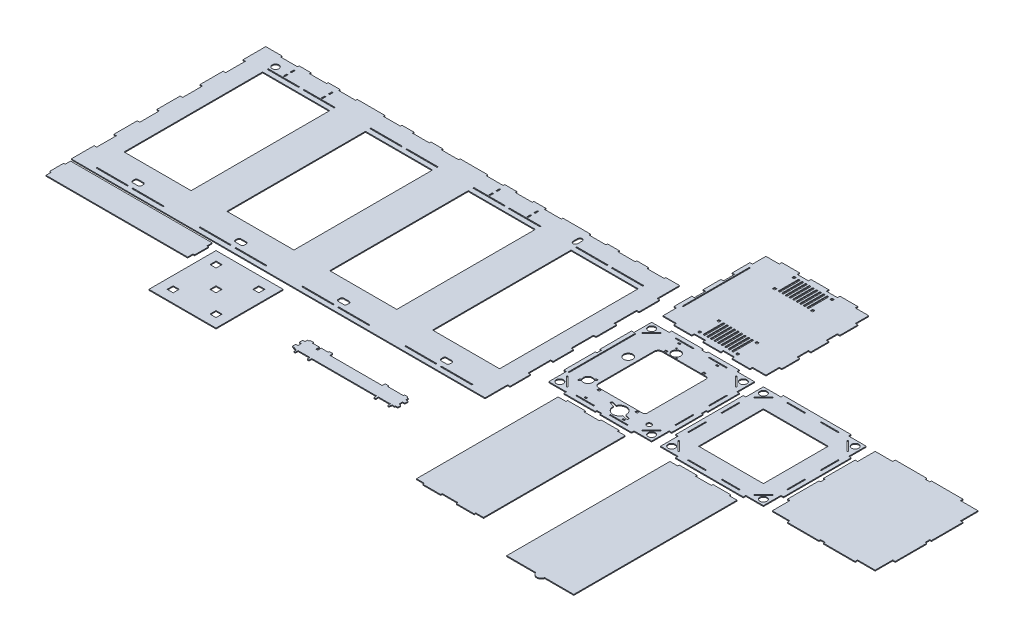
SolidWorks part; units mm, degrees
ref_plane "Front" through (0, 0, 0) normal (0, 0, 1) x (1, 0, 0)
ref_plane "Top" through (0, 0, 0) normal (0, 1, 0) x (1, 0, 0)
ref_plane "Right" through (0, 0, 0) normal (1, 0, 0) x (0, 0, -1)
sketch "Sketch1" plane through (0, 0, 0) normal (0, 1, 0) x (1, 0, 0)
  line L0 (0, 0) -> (438.15, 0) construction
  line L2 (-146.05, 276.225) -> (-146.05, -276.225) construction
  line L4 (146.05, 276.225) -> (146.05, -276.225) construction
  line L5 (-146.05, 276.225) -> (146.05, -276.225) construction
  line L6 (-146.05, -276.225) -> (146.05, 276.225) construction
  line L11 (146.05, 276.225) -> (438.15, 276.225)
  line L12 (146.05, 276.225) -> (146.05, -276.225) construction
  line L13 (146.05, -276.225) -> (438.15, -276.225)
  line L14 (438.15, 276.225) -> (438.15, -276.225) construction
  line L19 (-146.05, -276.225) -> (-438.15, -276.225)
  line L20 (-146.05, -276.225) -> (-146.05, 276.225) construction
  line L21 (-146.05, 276.225) -> (-438.15, 276.225)
  line L28 (146.05, -276.225) -> (-146.05, -276.225)
  line L34 (146.05, 276.225) -> (-146.05, 276.225)
  line L35 (-438.15, 276.225) -> (-438.15, -276.225) construction
  line L43 (-438.15, 276.225) -> (-730.25, 276.225)
  line L44 (-730.25, 276.225) -> (-730.25, -276.225) construction
  line L45 (-730.25, -276.225) -> (-438.15, -276.225)
  line L46 (438.15, 276.225) -> (438.15, 212.3694)
  line L47 (438.15, 212.3694) -> (445.262, 212.3694)
  line L48 (445.262, 212.3694) -> (445.262, 154.0764)
  line L49 (445.262, 154.0764) -> (438.15, 154.0764)
  line L50 (438.15, 154.0764) -> (438.15, 90.2208)
  line L51 (438.15, 90.2208) -> (445.262, 90.2208)
  line L63 (445.262, 90.2208) -> (445.262, 31.9278)
  line L64 (445.262, 31.9278) -> (438.15, 31.9278)
  line L65 (438.15, 31.9278) -> (438.15, -31.9278)
  line L66 (438.15, -31.9278) -> (445.262, -31.9278)
  line L67 (445.262, -31.9278) -> (445.262, -90.2208)
  line L68 (445.262, -90.2208) -> (438.15, -90.2208)
  line L69 (438.15, -90.2208) -> (438.15, -154.0764)
  line L70 (438.15, -154.0764) -> (445.262, -154.0764)
  line L71 (445.262, -154.0764) -> (445.262, -212.3694)
  line L72 (445.262, -212.3694) -> (438.15, -212.3694)
  line L73 (438.15, -212.3694) -> (438.15, -276.225)
  line L74 (-730.25, 276.225) -> (-737.362, 276.225)
  line L76 (-737.362, 211.1629) -> (-730.25, 211.1629)
  line L78 (-730.25, 155.2829) -> (-737.362, 155.2829)
  line L80 (-737.362, 89.0143) -> (-730.25, 89.0143)
  line L82 (-730.25, 33.1343) -> (-737.362, 33.1343)
  line L84 (-737.362, -33.1343) -> (-730.25, -33.1343)
  line L86 (-730.25, -89.0143) -> (-737.362, -89.0143)
  line L88 (-737.362, -155.2829) -> (-730.25, -155.2829)
  line L90 (-730.25, -211.1629) -> (-737.362, -211.1629)
  line L92 (-737.362, -276.225) -> (-730.25, -276.225)
  line L93 (445.262, 61.0743) -> (-730.25, 61.0743) construction
  line L94 (-730.25, 183.2229) -> (445.262, 183.2229) construction
  line L95 (-737.362, 276.225) -> (-737.362, 211.1629)
  line L96 (-737.362, 155.2829) -> (-737.362, 89.0143)
  line L97 (-730.25, 211.1629) -> (-730.25, 155.2829)
  line L98 (-730.25, 89.0143) -> (-730.25, 33.1343)
  line L99 (-730.25, -33.1343) -> (-730.25, -89.0143)
  line L100 (-730.25, -155.2829) -> (-730.25, -211.1629)
  line L101 (-730.25, -183.2229) -> (445.262, -183.2229) construction
  line L102 (-730.25, -61.0743) -> (445.262, -61.0743) construction
  line L103 (-737.362, 33.1343) -> (-737.362, -33.1343)
  line L104 (-737.362, -89.0143) -> (-737.362, -155.2829)
  line L105 (-737.362, -211.1629) -> (-737.362, -276.225)
  point P0 (0, 0)
  dimension "D1" = 292.1
  dimension "D2" = 552.45
  dimension "D3" = 7.112
  dimension "D4" = 58.293
  dimension "D5" = 55.88
extrude "Boss-Extrude1" add sketch "Sketch1" along normal blind 2.54
sketch "Sketch4" plane through (0, 2.54, 0) normal (0, 1, 0) x (1, 0, 0)
  line L0 (-438.15, 276.225) -> (-438.15, -276.225) construction
  line L1 (-438.15, 276.225) -> (-438.15, -276.225)
  line L2 (-146.05, 276.225) -> (-146.05, -276.225) construction
  line L3 (-146.05, 276.225) -> (-146.05, -276.225)
  line L4 (146.05, 276.225) -> (146.05, -276.225) construction
  line L5 (146.05, 276.225) -> (146.05, -276.225)
sketch "Sketch5" plane through (0, 2.54, 0) normal (0, 1, 0) x (1, 0, 0)
  line L0 (-730.25, -33.1343) -> (-730.25, 33.1343) construction
  line L1 (-438.15, 0) -> (-730.25, 0) construction
  line L2 (-438.15, 276.225) -> (-438.15, -276.225) construction
  line L3 (-438.15, 0) -> (-146.05, 0) construction
  line L4 (-146.05, 276.225) -> (-146.05, -276.225) construction
  line L5 (-146.05, 0) -> (146.05, 0) construction
  line L6 (146.05, 276.225) -> (146.05, -276.225) construction
  line L7 (146.05, 0) -> (438.15, 0) construction
  line L8 (438.15, -31.9278) -> (438.15, 31.9278) construction
  line L9 (-584.2, 12.6492) -> (-584.2, -276.225) construction
  line L10 (-737.362, -276.225) -> (438.15, -276.225) construction
  line L11 (-292.1, 12.6492) -> (-292.1, -276.225) construction
  line L12 (0, 12.6492) -> (0, -276.225) construction
  line L13 (292.1, 12.6492) -> (292.1, -276.225) construction
  line L14 (-488.95, -263.525) -> (-488.95, -276.225) construction
  line L15 (-679.45, -260.4008) -> (-488.95, -260.4008)
  line L16 (-679.45, -260.4008) -> (-679.45, -263.525)
  line L17 (-679.45, -263.525) -> (-488.95, -263.525)
  line L18 (-488.95, -260.4008) -> (-488.95, -263.525)
  line L19 (-679.45, -260.4008) -> (-488.95, -263.525) construction
  line L20 (-679.45, -263.525) -> (-488.95, -260.4008) construction
  line L21 (-387.35, -260.4008) -> (-196.85, -260.4008)
  line L22 (-387.35, -260.4008) -> (-387.35, -263.525)
  line L23 (-387.35, -263.525) -> (-196.85, -263.525)
  line L24 (-196.85, -260.4008) -> (-196.85, -263.525)
  line L25 (-387.35, -260.4008) -> (-196.85, -263.525) construction
  line L26 (-387.35, -263.525) -> (-196.85, -260.4008) construction
  line L27 (-95.25, -263.525) -> (95.25, -263.525)
  line L28 (-95.25, -263.525) -> (-95.25, -260.4008)
  line L29 (-95.25, -260.4008) -> (95.25, -260.4008)
  line L30 (95.25, -263.525) -> (95.25, -260.4008)
  line L31 (-95.25, -263.525) -> (95.25, -260.4008) construction
  line L32 (-95.25, -260.4008) -> (95.25, -263.525) construction
  line L33 (196.85, -263.525) -> (387.35, -263.525)
  line L34 (196.85, -263.525) -> (196.85, -260.4008)
  line L35 (196.85, -260.4008) -> (387.35, -260.4008)
  line L36 (387.35, -263.525) -> (387.35, -260.4008)
  line L37 (196.85, -263.525) -> (387.35, -260.4008) construction
  line L38 (196.85, -260.4008) -> (387.35, -263.525) construction
  line L39 (196.85, 260.4008) -> (387.35, 263.525) construction
  line L40 (196.85, 263.525) -> (387.35, 260.4008) construction
  line L41 (-95.25, 260.4008) -> (95.25, 263.525) construction
  line L42 (-95.25, 263.525) -> (95.25, 260.4008) construction
  line L43 (-387.35, 263.525) -> (-196.85, 260.4008) construction
  line L44 (-387.35, 260.4008) -> (-196.85, 263.525) construction
  line L45 (-679.45, 263.525) -> (-488.95, 260.4008) construction
  line L46 (-679.45, 260.4008) -> (-488.95, 263.525) construction
  line L47 (-584.2, 12.6492) -> (-584.2, 223.7613) construction
  line L48 (387.35, 263.525) -> (387.35, 260.4008) construction
  line L49 (196.85, 260.4008) -> (387.35, 260.4008) construction
  line L50 (196.85, 263.525) -> (196.85, 260.4008) construction
  line L51 (196.85, 263.525) -> (387.35, 263.525) construction
  line L52 (95.25, 263.525) -> (95.25, 260.4008) construction
  line L53 (-95.25, 260.4008) -> (95.25, 260.4008) construction
  line L54 (-95.25, 263.525) -> (-95.25, 260.4008) construction
  line L55 (-95.25, 263.525) -> (95.25, 263.525) construction
  line L56 (-196.85, 260.4008) -> (-196.85, 263.525) construction
  line L57 (-387.35, 263.525) -> (-196.85, 263.525) construction
  line L58 (-387.35, 260.4008) -> (-387.35, 263.525) construction
  line L59 (-387.35, 260.4008) -> (-196.85, 260.4008) construction
  line L60 (-488.95, 260.4008) -> (-488.95, 263.525) construction
  line L61 (-679.45, 263.525) -> (-488.95, 263.525) construction
  line L62 (-679.45, 260.4008) -> (-679.45, 263.525) construction
  line L63 (-679.45, 260.4008) -> (-488.95, 260.4008) construction
  line L64 (-292.1, 12.6492) -> (-292.1, 223.7613) construction
  line L65 (-679.45, 209.4992) -> (-488.95, 209.4992)
  line L66 (-679.45, 209.4992) -> (-679.45, -184.2008)
  line L67 (-679.45, -184.2008) -> (-488.95, -184.2008)
  line L68 (-488.95, 209.4992) -> (-488.95, -184.2008)
  line L69 (-679.45, 209.4992) -> (-488.95, -184.2008) construction
  line L70 (-679.45, -184.2008) -> (-488.95, 209.4992) construction
  line L71 (-387.35, 209.4992) -> (-196.85, 209.4992)
  line L72 (-387.35, 209.4992) -> (-387.35, -184.2008)
  line L73 (-387.35, -184.2008) -> (-196.85, -184.2008)
  line L74 (-196.85, 209.4992) -> (-196.85, -184.2008)
  line L75 (-387.35, 209.4992) -> (-196.85, -184.2008) construction
  line L76 (-387.35, -184.2008) -> (-196.85, 209.4992) construction
  line L77 (-95.25, 209.4992) -> (95.25, 209.4992)
  line L78 (-95.25, 209.4992) -> (-95.25, -184.2008)
  line L79 (-95.25, -184.2008) -> (95.25, -184.2008)
  line L80 (95.25, 209.4992) -> (95.25, -184.2008)
  line L81 (-95.25, 209.4992) -> (95.25, -184.2008) construction
  line L82 (-95.25, -184.2008) -> (95.25, 209.4992) construction
  line L83 (196.85, 209.4992) -> (387.35, 209.4992)
  line L84 (196.85, 209.4992) -> (196.85, -184.2008)
  line L85 (196.85, -184.2008) -> (387.35, -184.2008)
  line L86 (387.35, 209.4992) -> (387.35, -184.2008)
  line L87 (196.85, 209.4992) -> (387.35, -184.2008) construction
  line L88 (196.85, -184.2008) -> (387.35, 209.4992) construction
  line L89 (0, 12.6492) -> (0, 223.7613) construction
  line L90 (292.1, 12.6492) -> (292.1, 223.7613) construction
  line L91 (-387.35, -184.2008) -> (-387.35, -260.4008) construction
  line L92 (-679.45, 225.3234) -> (-488.95, 225.3234)
  line L93 (-679.45, 225.3234) -> (-679.45, 222.1992)
  line L94 (-679.45, 222.1992) -> (-488.95, 222.1992)
  line L95 (-488.95, 225.3234) -> (-488.95, 222.1992)
  line L96 (-679.45, 225.3234) -> (-488.95, 222.1992) construction
  line L97 (-679.45, 222.1992) -> (-488.95, 225.3234) construction
  line L98 (-387.35, 225.3234) -> (-196.85, 225.3234)
  line L99 (-387.35, 225.3234) -> (-387.35, 222.1992)
  line L100 (-387.35, 222.1992) -> (-196.85, 222.1992)
  line L101 (-196.85, 225.3234) -> (-196.85, 222.1992)
  line L102 (-387.35, 225.3234) -> (-196.85, 222.1992) construction
  line L103 (-387.35, 222.1992) -> (-196.85, 225.3234) construction
  line L104 (-95.25, 225.3234) -> (95.25, 225.3234)
  line L105 (-95.25, 225.3234) -> (-95.25, 222.1992)
  line L106 (-95.25, 222.1992) -> (95.25, 222.1992)
  line L107 (95.25, 225.3234) -> (95.25, 222.1992)
  line L108 (-95.25, 225.3234) -> (95.25, 222.1992) construction
  line L109 (-95.25, 222.1992) -> (95.25, 225.3234) construction
  line L110 (196.85, 225.3234) -> (387.35, 225.3234)
  line L111 (196.85, 225.3234) -> (196.85, 222.1992)
  line L112 (196.85, 222.1992) -> (387.35, 222.1992)
  line L113 (387.35, 225.3234) -> (387.35, 222.1992)
  line L114 (196.85, 225.3234) -> (387.35, 222.1992) construction
  line L115 (196.85, 222.1992) -> (387.35, 225.3234) construction
  line L116 (-196.85, -184.2008) -> (-196.85, -260.4008) construction
  line L117 (-196.85, -222.3008) -> (-387.35, -222.3008) construction
  line L118 (-7.62, -247.7008) -> (7.62, -247.7008)
  line L119 (-299.72, -231.8258) -> (-284.48, -231.8258)
  line L120 (-304.8, -236.9058) -> (-304.8, -242.6208)
  line L121 (-299.72, -247.7008) -> (-284.48, -247.7008)
  line L122 (-279.4, -236.9058) -> (-279.4, -242.6208)
  line L123 (-304.8, -231.8258) -> (-279.4, -247.7008) construction
  line L124 (-304.8, -247.7008) -> (-279.4, -231.8258) construction
  line L125 (-12.7, -236.9058) -> (-12.7, -242.6208)
  line L126 (-7.62, -231.8258) -> (7.62, -231.8258)
  line L127 (12.7, -236.9058) -> (12.7, -242.6208)
  line L128 (284.48, -247.7008) -> (299.72, -247.7008)
  line L129 (279.4, -236.9058) -> (279.4, -242.6208)
  line L130 (284.48, -231.8258) -> (299.72, -231.8258)
  line L131 (304.8, -236.9058) -> (304.8, -242.6208)
  line L132 (-596.9, -236.9058) -> (-596.9, -242.6208)
  line L133 (-591.82, -231.8258) -> (-576.58, -231.8258)
  line L134 (-571.5, -236.9058) -> (-571.5, -242.6208)
  line L135 (-591.82, -247.7008) -> (-576.58, -247.7008)
  line L136 (438.15, 276.225) -> (-737.362, 276.225) construction
  line L137 (184.15, 246.9134) -> (184.15, 234.2134) construction
  line L138 (190.5, 246.9134) -> (190.5, 234.2134)
  line L139 (177.8, 246.9134) -> (177.8, 234.2134)
  line L141 (-737.362, 276.225) -> (-737.362, 211.1629) construction
  line L142 (184.15, 240.5634) -> (-673.862, 240.5634) construction
  arc A0 (-284.48, -231.8258) -> (-279.4, -236.9058) centre (-284.48, -236.9058) cw
  arc A1 (-279.4, -242.6208) -> (-284.48, -247.7008) centre (-284.48, -242.6208) cw
  arc A2 (-299.72, -247.7008) -> (-304.8, -242.6208) centre (-299.72, -242.6208) cw
  arc A3 (-304.8, -236.9058) -> (-299.72, -231.8258) centre (-299.72, -236.9058) cw
  arc A4 (-7.62, -247.7008) -> (-12.7, -242.6208) centre (-7.62, -242.6208) cw
  arc A5 (-12.7, -236.9058) -> (-7.62, -231.8258) centre (-7.62, -236.9058) cw
  arc A6 (7.62, -231.8258) -> (12.7, -236.9058) centre (7.62, -236.9058) cw
  arc A7 (12.7, -242.6208) -> (7.62, -247.7008) centre (7.62, -242.6208) cw
  arc A8 (284.48, -247.7008) -> (279.4, -242.6208) centre (284.48, -242.6208) cw
  arc A9 (279.4, -236.9058) -> (284.48, -231.8258) centre (284.48, -236.9058) cw
  arc A10 (299.72, -231.8258) -> (304.8, -236.9058) centre (299.72, -236.9058) cw
  arc A11 (304.8, -242.6208) -> (299.72, -247.7008) centre (299.72, -242.6208) cw
  arc A12 (-596.9, -236.9058) -> (-591.82, -231.8258) centre (-591.82, -236.9058) cw
  arc A13 (-591.82, -247.7008) -> (-596.9, -242.6208) centre (-591.82, -242.6208) cw
  arc A14 (-576.58, -231.8258) -> (-571.5, -236.9058) centre (-576.58, -236.9058) cw
  arc A15 (-571.5, -242.6208) -> (-576.58, -247.7008) centre (-576.58, -242.6208) cw
  arc A16 (190.5, 246.9134) -> (177.8, 246.9134) centre (184.15, 246.9134) ccw
  arc A17 (177.8, 234.2134) -> (190.5, 234.2134) centre (184.15, 234.2134) ccw
  circle A18 centre (-673.862, 240.5634) radius 9.525
  point P27 (-584.2, -261.9629)
  point P32 (-292.1, -261.9629)
  point P37 (0, -261.9629)
  point P42 (292.1, -261.9629)
  point P66 (292.1, 261.9629)
  point P67 (0, 261.9629)
  point P68 (-292.1, 261.9629)
  point P69 (-584.2, 261.9629)
  point P106 (-292.1, -239.7633)
  point P148 (0, -247.7008)
  point P161 (-584.2, -247.7008)
  point P165 (184.15, 240.5634)
  point P175 (-497.5445, -226.3745)
  point P176 (-584.2, 0)
  point P177 (-488.95, -217.224)
  point P178 (-292.1, 0)
  point P179 (0, 0)
  point P180 (292.1, 0)
  dimension "D5" = 12.7
  dimension "D7" = 15.875
  dimension "D9" = 5.08
  dimension "D14" = 25.4
  dimension "D16" = 2.54
  dimension "D17" = 19.05
  dimension "D18" = 63.5
  dimension "D1" = 12.7
  dimension "D2" = 3.1242
  dimension "D3" = 190.5
  dimension "D4" = 393.7
  dimension "D6" = 12.7
  dimension "D8" = 25.4
  dimension "D10" = 3
  dimension "D12" = 50.9016
  dimension "D13" = 12.7
  dimension "D15" = 38.1
  dimension "D19" = 190.5
  dimension "D20" = 76.2
  dimension "D11" = 2
extrude "Cut-Extrude2" cut sketch "Sketch5" against normal through all
sketch "Sketch6" plane through (0, 0, 0) normal (0, 1, 0) x (1, 0, 0)
  line L0 (0, 0) -> (635, 0) construction
  line L1 (635, 0) -> (635, 149.606) construction
  line L2 (488.95, 146.05) -> (781.05, 146.05) construction
  line L3 (488.95, 146.05) -> (488.95, -146.05) construction
  line L4 (488.95, -146.05) -> (781.05, -146.05) construction
  line L5 (781.05, 146.05) -> (781.05, -146.05) construction
  line L6 (488.95, 146.05) -> (781.05, -146.05) construction
  line L7 (488.95, -146.05) -> (781.05, 146.05) construction
  line L8 (635, 0) -> (784.606, 0) construction
  line L9 (635, 0) -> (635, -149.606) construction
  line L10 (488.95, 96.139) -> (488.95, 146.05)
  line L11 (538.861, 153.162) -> (731.139, 153.162)
  line L12 (538.861, 153.162) -> (538.861, 146.05)
  line L13 (538.861, 146.05) -> (731.139, 146.05) construction
  line L14 (731.139, 153.162) -> (731.139, 146.05)
  line L15 (538.861, 153.162) -> (731.139, 146.05) construction
  line L16 (538.861, 146.05) -> (731.139, 153.162) construction
  line L17 (788.162, -96.139) -> (781.05, -96.139)
  line L18 (788.162, -96.139) -> (788.162, 96.139)
  line L19 (788.162, 96.139) -> (781.05, 96.139)
  line L20 (781.05, -96.139) -> (781.05, 96.139) construction
  line L21 (788.162, -96.139) -> (781.05, 96.139) construction
  line L22 (788.162, 96.139) -> (781.05, -96.139) construction
  line L23 (538.861, -153.162) -> (731.139, -153.162)
  line L24 (538.861, -153.162) -> (538.861, -146.05)
  line L25 (538.861, -146.05) -> (731.139, -146.05) construction
  line L26 (731.139, -153.162) -> (731.139, -146.05)
  line L27 (538.861, -153.162) -> (731.139, -146.05) construction
  line L28 (538.861, -146.05) -> (731.139, -153.162) construction
  line L29 (481.838, 96.139) -> (488.95, 96.139)
  line L30 (481.838, 96.139) -> (481.838, -96.139)
  line L31 (481.838, -96.139) -> (488.95, -96.139)
  line L32 (488.95, 96.139) -> (488.95, -96.139) construction
  line L33 (481.838, 96.139) -> (488.95, -96.139) construction
  line L34 (481.838, -96.139) -> (488.95, 96.139) construction
  line L35 (488.95, 146.05) -> (538.861, 146.05)
  line L36 (731.139, 146.05) -> (781.05, 146.05)
  line L37 (781.05, 146.05) -> (781.05, 96.139)
  line L38 (781.05, -96.139) -> (781.05, -146.05)
  line L39 (781.05, -146.05) -> (731.139, -146.05)
  line L40 (538.861, -146.05) -> (488.95, -146.05)
  line L41 (488.95, -146.05) -> (488.95, -96.139)
  line L42 (799.338, 96.139) -> (799.338, -96.139)
  line L43 (799.338, 96.139) -> (806.45, 96.139)
  line L44 (806.45, 96.139) -> (806.45, 146.05)
  line L45 (806.45, 146.05) -> (856.361, 146.05)
  line L46 (856.361, 153.162) -> (856.361, 146.05)
  line L47 (856.361, 153.162) -> (1048.639, 153.162)
  line L48 (1048.639, 153.162) -> (1048.639, 146.05)
  line L49 (1048.639, 146.05) -> (1098.55, 146.05)
  line L50 (1098.55, 146.05) -> (1098.55, 96.139)
  line L51 (1105.662, 96.139) -> (1098.55, 96.139)
  line L52 (1105.662, -96.139) -> (1105.662, 96.139)
  line L53 (1105.662, -96.139) -> (1098.55, -96.139)
  line L54 (1098.55, -96.139) -> (1098.55, -146.05)
  line L55 (1098.55, -146.05) -> (1048.639, -146.05)
  line L56 (1048.639, -153.162) -> (1048.639, -146.05)
  line L57 (856.361, -153.162) -> (1048.639, -153.162)
  line L58 (856.361, -153.162) -> (856.361, -146.05)
  line L59 (856.361, -146.05) -> (806.45, -146.05)
  line L60 (806.45, -146.05) -> (806.45, -96.139)
  line L61 (799.338, -96.139) -> (806.45, -96.139)
  line L62 (806.45, 146.05) -> (1098.55, -146.05) construction
  line L63 (1116.838, 96.139) -> (1116.838, -96.139)
  line L64 (1116.838, 96.139) -> (1123.95, 96.139)
  line L65 (1123.95, 96.139) -> (1123.95, 146.05)
  line L66 (1123.95, 146.05) -> (1173.861, 146.05)
  line L67 (1173.861, 153.162) -> (1173.861, 146.05)
  line L68 (1173.861, 153.162) -> (1366.139, 153.162)
  line L69 (1366.139, 153.162) -> (1366.139, 146.05)
  line L70 (1366.139, 146.05) -> (1416.05, 146.05)
  line L71 (1416.05, 146.05) -> (1416.05, 96.139)
  line L72 (1423.162, 96.139) -> (1416.05, 96.139)
  line L73 (1423.162, -96.139) -> (1423.162, 96.139)
  line L74 (1423.162, -96.139) -> (1416.05, -96.139)
  line L75 (1416.05, -96.139) -> (1416.05, -146.05)
  line L76 (1416.05, -146.05) -> (1366.139, -146.05)
  line L77 (1366.139, -153.162) -> (1366.139, -146.05)
  line L78 (1173.861, -153.162) -> (1366.139, -153.162)
  line L79 (1173.861, -153.162) -> (1173.861, -146.05)
  line L80 (1173.861, -146.05) -> (1123.95, -146.05)
  line L81 (1123.95, -146.05) -> (1123.95, -96.139)
  line L82 (1116.838, -96.139) -> (1123.95, -96.139)
  line L83 (1270, 153.162) -> (1270, -153.162) construction
  line L84 (860.425, 92.075) -> (1044.575, 92.075)
  line L85 (860.425, 92.075) -> (860.425, -92.075)
  line L86 (860.425, -92.075) -> (1044.575, -92.075)
  line L87 (1044.575, 92.075) -> (1044.575, -92.075)
  line L88 (860.425, 92.075) -> (1044.575, -92.075) construction
  line L89 (860.425, -92.075) -> (1044.575, 92.075) construction
  point P22 (485.394, 0)
  point P67 (952.5, 0)
  dimension "D1" = 292.1
  dimension "D2" = 292.1
  dimension "D3" = 7.112
  dimension "D4" = 192.278
  dimension "D5" = 635
  dimension "D7" = 317.5
  dimension "D8" = 184.15
  dimension "D9" = 11.176
  dimension "D6" = 3
extrude "Boss-Extrude2" add sketch "Sketch6" along normal blind 2.54 separate body
sketch "Sketch7" plane through (0, 0, 0) normal (0, 1, 0) x (1, 0, 0)
  line L0 (-679.45, 222.1992) -> (-679.45, -180.1368) construction
  line L1 (-732.917, -282.575) -> (-330.581, -282.575)
  line L2 (-732.917, -282.575) -> (-732.917, -297.815)
  line L3 (-732.917, -352.425) -> (-330.581, -352.425)
  line L4 (-330.581, -282.575) -> (-330.581, -297.815)
  line L5 (-732.917, -282.575) -> (-330.581, -352.425) construction
  line L6 (-732.917, -352.425) -> (-330.581, -282.575) construction
  line L7 (-679.45, 209.4992) -> (-679.45, -184.2008) construction
  line L8 (-679.45, -180.1368) -> (-679.45, -184.2008) construction
  line L9 (488.95, -96.139) -> (488.95, -146.05) construction
  line L10 (488.95, -146.05) -> (538.861, -146.05) construction
  line L12 (-732.917, -297.815) -> (-737.362, -297.815)
  line L13 (502.6443, -105.415) -> (529.585, -132.3557) construction
  line L14 (502.6443, -105.415) -> (500.4351, -107.6241) construction
  line L15 (500.4351, -107.6241) -> (527.3759, -134.5649) construction
  line L16 (529.585, -132.3557) -> (527.3759, -134.5649) construction
  line L17 (502.6443, -105.415) -> (527.3759, -134.5649) construction
  line L18 (500.4351, -107.6241) -> (529.585, -132.3557) construction
  line L19 (-737.362, -297.815) -> (-737.362, -337.185)
  line L20 (-737.362, -337.185) -> (-732.917, -337.185)
  line L21 (488.95, -96.139) -> (538.861, -146.05) construction
  line L22 (515.0101, -119.9899) -> (513.9055, -121.0945) construction
  line L23 (-732.917, -337.185) -> (-732.917, -352.425)
  line L24 (-330.581, -297.815) -> (-326.136, -297.815)
  line L25 (-326.136, -297.815) -> (-326.136, -337.185)
  line L26 (-326.136, -337.185) -> (-330.581, -337.185)
  line L27 (-330.581, -337.185) -> (-330.581, -352.425)
  line L28 (-737.362, -276.225) -> (438.15, -276.225) construction
  line L29 (-737.362, -211.1629) -> (-737.362, -276.225) construction
  point P0 (-531.749, -317.5)
  point P14 (515.0101, -119.9899)
  dimension "D1" = 69.85
  dimension "D2" = 4.064
  dimension "D3" = 3.1242
  dimension "D4" = 39.37
  dimension "D5" = 38.1
  dimension "D6" = 4.445
  dimension "D7" = 6.35
extrude "Boss-Extrude3" add sketch "Sketch7" along normal blind 2.54 separate body
sketch "Sketch8" plane through (0, 2.54, 0) normal (0, 1, 0) x (1, 0, 0)
  line L0 (500.4351, -107.6241) -> (527.3759, -134.5649) construction
  line L1 (529.585, -132.3557) -> (527.3759, -134.5649) construction
  line L2 (502.6443, -105.415) -> (529.585, -132.3557) construction
  line L3 (502.6443, -105.415) -> (500.4351, -107.6241) construction
  line L4 (500.4351, -107.6241) -> (527.3759, -134.5649)
  line L5 (529.585, -132.3557) -> (527.3759, -134.5649)
  line L6 (502.6443, -105.415) -> (529.585, -132.3557)
  line L7 (502.6443, -105.415) -> (500.4351, -107.6241)
  line L8 (488.95, 146.05) -> (781.05, -146.05) construction
  line L9 (529.585, 132.3557) -> (502.6443, 105.415)
  line L10 (529.585, 132.3557) -> (527.3759, 134.5649)
  line L11 (527.3759, 134.5649) -> (500.4351, 107.6241)
  line L12 (502.6443, 105.415) -> (500.4351, 107.6241)
  line L13 (767.3557, 105.415) -> (740.415, 132.3557)
  line L14 (767.3557, 105.415) -> (769.5649, 107.6241)
  line L15 (769.5649, 107.6241) -> (742.6241, 134.5649)
  line L16 (740.415, 132.3557) -> (742.6241, 134.5649)
  line L17 (740.415, -132.3557) -> (767.3557, -105.415)
  line L18 (740.415, -132.3557) -> (742.6241, -134.5649)
  line L19 (742.6241, -134.5649) -> (769.5649, -107.6241)
  line L20 (767.3557, -105.415) -> (769.5649, -107.6241)
  line L21 (806.45, -96.139) -> (856.361, -146.05) construction
  line L22 (817.9351, -107.6241) -> (820.1443, -105.415)
  line L23 (820.1443, -105.415) -> (847.085, -132.3557)
  line L24 (847.085, -132.3557) -> (844.8759, -134.5649)
  line L25 (831.4055, -121.0945) -> (833.6146, -118.8854) construction
  line L26 (817.9351, -107.6241) -> (844.8759, -134.5649)
  line L27 (806.45, 146.05) -> (1098.55, -146.05) construction
  line L28 (820.1443, 105.415) -> (817.9351, 107.6241)
  line L29 (844.8759, 134.5649) -> (817.9351, 107.6241)
  line L30 (844.8759, 134.5649) -> (847.085, 132.3557)
  line L31 (847.085, 132.3557) -> (820.1443, 105.415)
  line L32 (1057.915, 132.3557) -> (1060.1241, 134.5649)
  line L33 (1087.0649, 107.6241) -> (1060.1241, 134.5649)
  line L34 (1087.0649, 107.6241) -> (1084.8557, 105.415)
  line L35 (1084.8557, 105.415) -> (1057.915, 132.3557)
  line L36 (1084.8557, -105.415) -> (1087.0649, -107.6241)
  line L37 (1060.1241, -134.5649) -> (1087.0649, -107.6241)
  line L38 (1060.1241, -134.5649) -> (1057.915, -132.3557)
  line L39 (1057.915, -132.3557) -> (1084.8557, -105.415)
  circle A0 centre (635, 0) radius 20.7898 construction
  circle A1 centre (635, 0) radius 20.7898 construction
  circle A2 centre (635, 0) radius 20.7898 construction
  circle A3 centre (635, 0) radius 20.7898 construction
  circle A4 centre (952.5, 0) radius 130.2137 construction
  circle A5 centre (822.1654, 130.3346) radius 10
  circle A9 centre (1082.8346, 130.3346) radius 10
  circle A10 centre (1082.8346, -130.3346) radius 10
  circle A11 centre (822.1654, -130.3346) radius 10
  circle A12 centre (504.6654, 130.3346) radius 10
  circle A13 centre (765.3346, 130.3346) radius 10
  circle A14 centre (765.3346, -130.3346) radius 10
  circle A15 centre (504.6654, -130.3346) radius 10
  point P28 (635, 0)
  point P58 (952.5, 0)
  point P67 (952.5, 0)
  point P76 (635, 0)
  dimension "D3" = 20
  dimension "D4" = 22.225
  dimension "D6" = 22.225
  dimension "D1" = 4
  dimension "D2" = 4
  dimension "D5" = 4
  dimension "D7" = 4
extrude "Cut-Extrude3" cut sketch "Sketch8" against normal through all
sketch "Sketch9" plane through (0, 0, 0) normal (0, 1, 0) x (1, 0, 0)
  line L0 (-737.362, -276.225) -> (438.15, -276.225) construction
  line L1 (-306.136, -296.225) -> (-115.636, -296.225)
  line L2 (-306.136, -296.225) -> (-306.136, -486.725)
  line L3 (-306.136, -486.725) -> (-115.636, -486.725)
  line L4 (-115.636, -296.225) -> (-115.636, -486.725)
  line L5 (-306.136, -296.225) -> (-115.636, -486.725) construction
  line L6 (-306.136, -486.725) -> (-115.636, -296.225) construction
  line L7 (-219.522, -382.839) -> (-202.25, -382.839)
  line L8 (-219.522, -382.839) -> (-219.522, -400.111)
  line L9 (-219.522, -400.111) -> (-202.25, -400.111)
  line L10 (-202.25, -382.839) -> (-202.25, -400.111)
  line L11 (-219.522, -382.839) -> (-202.25, -400.111) construction
  line L12 (-219.522, -400.111) -> (-202.25, -382.839) construction
  line L13 (-271.7847, -330.5763) -> (-149.9873, -330.5763) construction
  line L14 (-271.7847, -330.5763) -> (-271.7847, -452.3737) construction
  line L15 (-271.7847, -452.3737) -> (-149.9873, -452.3737) construction
  line L16 (-149.9873, -330.5763) -> (-149.9873, -452.3737) construction
  line L17 (-271.7847, -330.5763) -> (-149.9873, -452.3737) construction
  line L18 (-271.7847, -452.3737) -> (-149.9873, -330.5763) construction
  line L19 (-280.4207, -321.9403) -> (-263.1487, -321.9403)
  line L20 (-280.4207, -321.9403) -> (-280.4207, -339.2123)
  line L21 (-280.4207, -339.2123) -> (-263.1487, -339.2123)
  line L22 (-263.1487, -321.9403) -> (-263.1487, -339.2123)
  line L23 (-280.4207, -321.9403) -> (-263.1487, -339.2123) construction
  line L24 (-280.4207, -339.2123) -> (-263.1487, -321.9403) construction
  line L25 (-280.4207, -443.7377) -> (-263.1487, -443.7377)
  line L26 (-280.4207, -443.7377) -> (-280.4207, -461.0097)
  line L27 (-280.4207, -461.0097) -> (-263.1487, -461.0097)
  line L28 (-263.1487, -443.7377) -> (-263.1487, -461.0097)
  line L29 (-280.4207, -443.7377) -> (-263.1487, -461.0097) construction
  line L30 (-280.4207, -461.0097) -> (-263.1487, -443.7377) construction
  line L31 (-141.3513, -443.7377) -> (-158.6233, -443.7377)
  line L32 (-141.3513, -443.7377) -> (-141.3513, -461.0097)
  line L33 (-141.3513, -461.0097) -> (-158.6233, -461.0097)
  line L34 (-158.6233, -443.7377) -> (-158.6233, -461.0097)
  line L35 (-141.3513, -443.7377) -> (-158.6233, -461.0097) construction
  line L36 (-141.3513, -461.0097) -> (-158.6233, -443.7377) construction
  line L37 (-158.6233, -321.9403) -> (-141.3513, -321.9403)
  line L38 (-158.6233, -321.9403) -> (-158.6233, -339.2123)
  line L39 (-158.6233, -339.2123) -> (-141.3513, -339.2123)
  line L40 (-141.3513, -321.9403) -> (-141.3513, -339.2123)
  line L41 (-158.6233, -321.9403) -> (-141.3513, -339.2123) construction
  line L42 (-158.6233, -339.2123) -> (-141.3513, -321.9403) construction
  line L43 (-326.136, -337.185) -> (-326.136, -297.815) construction
  point P0 (-210.886, -391.475)
  point P5 (-210.886, -391.475)
  point P12 (-210.886, -391.475)
  dimension "D1" = 190.5
  dimension "D2" = 190.5
  dimension "D3" = 17.272
  dimension "D4" = 17.272
  dimension "D5" = 20
  dimension "D6" = 20
  dimension "D7" = 121.7975
extrude "Boss-Extrude4" add sketch "Sketch9" along normal blind 2.54 separate body
sketch "Sketch10" plane through (0, 2.54, 0) normal (0, 1, 0) x (1, 0, 0)
  line L4 (-488.95, 2.4892) -> (-488.95, 22.8092)
  line L5 (-196.85, 2.4892) -> (-196.85, 22.8092)
  line L6 (95.25, 2.4892) -> (95.25, 22.8092)
  line L7 (387.35, 2.4892) -> (387.35, 22.8092)
  line L8 (-679.45, -180.1368) -> (-488.95, -180.1368)
  line L9 (-584.2, -180.1368) -> (-584.2, -184.2008) construction
  line L14 (-679.45, 209.4992) -> (-679.45, -184.2008) construction
  line L15 (-488.95, -184.2008) -> (-488.95, 209.4992) construction
  line L16 (-679.45, -184.2008) -> (-488.95, -184.2008) construction
  line L17 (-387.35, -180.1368) -> (-196.85, -180.1368)
  line L18 (-387.35, 209.4992) -> (-387.35, -184.2008) construction
  line L19 (-196.85, -184.2008) -> (-196.85, 209.4992) construction
  line L20 (-95.25, -180.1368) -> (95.25, -180.1368)
  line L21 (-95.25, 209.4992) -> (-95.25, -184.2008) construction
  line L22 (95.25, -184.2008) -> (95.25, 209.4992) construction
  line L23 (196.85, -180.1368) -> (387.35, -180.1368)
  line L24 (196.85, 209.4992) -> (196.85, -184.2008) construction
  line L25 (387.35, -184.2008) -> (387.35, 209.4992) construction
  arc A0 (-488.95, 22.8092) -> (-488.95, 2.4892) centre (-488.95, 12.6492) ccw
  arc A1 (-196.85, 22.8092) -> (-196.85, 2.4892) centre (-196.85, 12.6492) ccw
  arc A2 (95.25, 22.8092) -> (95.25, 2.4892) centre (95.25, 12.6492) ccw
  arc A3 (387.35, 22.8092) -> (387.35, 2.4892) centre (387.35, 12.6492) ccw
  point P2 (-488.95, 40.1517)
  point P3 (0, 0)
  point P6 (0, 0)
  point P7 (0, 0)
  point P10 (-196.85, 123.8006)
  point P11 (95.25, 136.8668)
  point P14 (387.35, 150.7497)
  point P15 (0, 0)
  point P48 (0, 0)
  point P49 (0, 0)
  point P50 (0, 0)
  point P51 (-557.6288, 190.5)
  point P52 (0, 0)
  point P53 (0, 0)
  point P54 (-196.85, -10.16)
  point P55 (-196.85, 0)
  point P56 (-196.85, 10.16)
  point P57 (0, 0)
  point P58 (0, 0)
  dimension "D1" = 20.32
  dimension "D2" = 4.064
sketch "Sketch11" plane through (0, 2.54, 0) normal (0, 1, 0) x (1, 0, 0)
  line L0 (488.95, 146.05) -> (781.05, -146.05) construction
  line L18 (731.139, -146.05) -> (781.05, -146.05) construction
  line L19 (781.05, -146.05) -> (781.05, -96.139) construction
  line L109 (679.0012, -124.5383) -> (690.5024, -127.62)
  line L110 (692.0801, -121.7317) -> (680.579, -118.65)
  line L111 (642.245, -108.3784) -> (630.7438, -105.2967)
  line L112 (629.1661, -111.185) -> (640.6672, -114.2667)
  line L126 (551.6771, -78.5338) -> (554.4254, -75.7854)
  line L127 (550.8333, -72.1933) -> (548.085, -74.9417)
  line L128 (529.0957, -93.9309) -> (526.3474, -96.6793)
  line L129 (529.9395, -100.2714) -> (532.6878, -97.523)
  line L130 (699.863, 90.3227) -> (574.863, 90.3227)
  line L131 (563.5613, 79.021) -> (563.5613, -78.979)
  line L132 (574.863, -90.2808) -> (699.863, -90.2808)
  line L137 (706.1648, -83.979) -> (706.1648, 84.021)
  circle A0 centre (540.385, 28.067) radius 12.6875
  circle A1 centre (600.5844, 104.3237) radius 12.6875
  circle A2 centre (612.3808, 93.3292) radius 1.7055
  circle A3 centre (588.3905, 117.3172) radius 1.7055
  arc A4 (673.6061, -130.382) -> (677.5437, -125.183) centre (660.6231, -116.4583) ccw
  arc A5 (679.6391, -117.3629) -> (643.7025, -107.7337) centre (660.6231, -116.4583) ccw
  arc A6 (641.6071, -115.5538) -> (673.6061, -130.382) centre (660.6231, -116.4583) ccw
  arc A7 (706.1648, 84.021) -> (699.863, 90.3227) centre (699.863, 84.021) ccw
  arc A8 (699.863, -90.2808) -> (706.1648, -83.979) centre (699.863, -83.979) ccw
  arc A9 (563.5613, -78.979) -> (574.863, -90.2808) centre (574.863, -78.979) ccw
  arc A10 (574.863, 90.3227) -> (563.5613, 79.021) centre (574.863, 79.021) ccw
  circle A14 centre (540.385, 28.067) radius 12.6875 construction
  circle A15 centre (600.5844, 104.3237) radius 12.6875 construction
  circle A16 centre (612.3808, 93.3292) radius 1.7055 construction
  circle A17 centre (588.3905, 117.3172) radius 1.7055 construction
  circle A24 centre (737.0572, -109.22) radius 6.7474
  arc A97 (673.6061, -130.382) -> (677.5437, -125.183) centre (660.6231, -116.4583) ccw construction
  arc A98 (679.0012, -124.5383) -> (677.5437, -125.183) centre (678.6725, -125.765) ccw
  arc A99 (690.5024, -127.62) -> (692.0801, -121.7317) centre (691.2913, -124.6758) ccw
  arc A100 (679.6391, -117.3629) -> (680.579, -118.65) centre (680.9077, -117.4233) ccw
  arc A101 (679.6391, -117.3629) -> (643.7025, -107.7337) centre (660.6231, -116.4583) ccw construction
  arc A102 (642.245, -108.3784) -> (643.7025, -107.7337) centre (642.5737, -107.1517) ccw
  arc A103 (630.7438, -105.2967) -> (629.1661, -111.185) centre (629.955, -108.2408) ccw
  arc A104 (641.6071, -115.5538) -> (640.6672, -114.2667) centre (640.3385, -115.4934) ccw
  arc A105 (641.6071, -115.5538) -> (673.6061, -130.382) centre (660.6231, -116.4583) ccw construction
  arc A120 (551.6771, -78.5338) -> (551.466, -80.0506) centre (552.5751, -79.4318) ccw
  arc A121 (554.4254, -75.7854) -> (550.8333, -72.1933) centre (552.6294, -73.9893) ccw
  arc A122 (546.5682, -75.1527) -> (548.085, -74.9417) centre (547.1869, -74.0436) ccw
  arc A123 (546.5682, -75.1527) -> (529.3068, -92.4141) centre (540.3864, -86.2323) ccw
  arc A124 (529.0957, -93.9309) -> (529.3068, -92.4141) centre (528.1977, -93.0329) ccw
  arc A125 (526.3474, -96.6793) -> (529.9395, -100.2714) centre (528.1434, -98.4753) ccw
  arc A126 (534.2046, -97.312) -> (532.6878, -97.523) centre (533.5858, -98.421) ccw
  arc A127 (534.2046, -97.312) -> (551.466, -80.0506) centre (540.3864, -86.2323) ccw
  arc A128 (706.1648, 84.021) -> (699.863, 90.3227) centre (699.863, 84.021) ccw construction
  arc A129 (574.863, 90.3227) -> (563.5613, 79.021) centre (574.863, 79.021) ccw construction
  arc A130 (563.5613, -78.979) -> (574.863, -90.2808) centre (574.863, -78.979) ccw construction
  arc A166 (699.863, -90.2808) -> (706.1648, -83.979) centre (699.863, -83.979) ccw construction
  dimension "D1" = 13.4948
  dimension "D2" = 36.83
  dimension "D3" = 43.9928
  dimension "D4" = 6.5219
extrude "Cut-Extrude4" cut sketch "Sketch11" against normal through all
sketch "Sketch12" plane through (0, 2.54, 0) normal (0, 1, 0) x (1, 0, 0)
  line L0 (481.838, 0) -> (563.5613, 0.021) construction
  line L1 (481.838, 96.139) -> (481.838, -96.139) construction
  line L2 (563.5613, 79.021) -> (563.5613, -78.979) construction
  line L3 (494.0935, 95.2531) -> (494.0935, 0.0031) construction
  line L4 (492.633, 95.2531) -> (495.554, 95.2531) construction
  line L5 (492.633, 95.2531) -> (492.633, -95.2469) construction
  line L6 (492.633, -95.2469) -> (495.554, -95.2469) construction
  line L7 (495.554, 95.2531) -> (495.554, -95.2469) construction
  line L8 (492.633, 95.2531) -> (495.554, -95.2469) construction
  line L9 (492.633, -95.2469) -> (495.554, 95.2531) construction
  line L10 (494.0935, 0.0031) -> (494.0935, -95.2469) construction
  line L11 (488.95, 146.05) -> (781.05, -146.05) construction
  line L12 (492.633, -22.2219) -> (495.554, -22.2219)
  line L13 (492.633, -22.2219) -> (492.633, -73.0219)
  line L14 (492.633, -73.0219) -> (495.554, -73.0219)
  line L15 (495.554, -22.2219) -> (495.554, -73.0219)
  line L16 (492.633, -22.2219) -> (495.554, -73.0219) construction
  line L17 (492.633, -73.0219) -> (495.554, -22.2219) construction
  line L18 (492.633, 73.0281) -> (495.554, 73.0281)
  line L19 (492.633, 73.0281) -> (492.633, 22.2281)
  line L20 (492.633, 22.2281) -> (495.554, 22.2281)
  line L21 (495.554, 73.0281) -> (495.554, 22.2281)
  line L22 (492.633, 73.0281) -> (495.554, 22.2281) construction
  line L23 (492.633, 22.2281) -> (495.554, 73.0281) construction
  line L24 (708.0281, 142.367) -> (657.2281, 142.367)
  line L25 (612.7781, 142.367) -> (612.7781, 139.446)
  line L26 (612.7781, 142.367) -> (561.9781, 142.367)
  line L27 (612.7781, 139.446) -> (561.9781, 139.446)
  line L28 (708.0281, 139.446) -> (657.2281, 139.446)
  line L29 (657.2281, 142.367) -> (657.2281, 139.446)
  line L30 (708.0281, 142.367) -> (708.0281, 139.446)
  line L31 (561.9781, 142.367) -> (561.9781, 139.446)
  line L32 (777.367, -73.0281) -> (777.367, -22.2281)
  line L33 (777.367, 22.2219) -> (774.446, 22.2219)
  line L34 (777.367, 22.2219) -> (777.367, 73.0219)
  line L35 (774.446, 22.2219) -> (774.446, 73.0219)
  line L36 (774.446, -73.0281) -> (774.446, -22.2281)
  line L37 (777.367, -22.2281) -> (774.446, -22.2281)
  line L38 (777.367, -73.0281) -> (774.446, -73.0281)
  line L39 (777.367, 73.0219) -> (774.446, 73.0219)
  line L40 (561.9719, -142.367) -> (612.7719, -142.367)
  line L41 (657.2219, -142.367) -> (657.2219, -139.446)
  line L42 (657.2219, -142.367) -> (708.0219, -142.367)
  line L43 (657.2219, -139.446) -> (708.0219, -139.446)
  line L44 (561.9719, -139.446) -> (612.7719, -139.446)
  line L45 (612.7719, -142.367) -> (612.7719, -139.446)
  line L46 (561.9719, -142.367) -> (561.9719, -139.446)
  line L47 (708.0219, -142.367) -> (708.0219, -139.446)
  line L48 (799.338, 0) -> (860.425, 0) construction
  line L49 (799.338, 96.139) -> (799.338, -96.139) construction
  line L50 (860.425, 92.075) -> (860.425, -92.075) construction
  line L51 (495.554, 73.0281) -> (810.133, 73.0281) construction
  line L52 (495.554, -22.2219) -> (810.133, -22.2219) construction
  line L53 (810.133, 73.0281) -> (810.133, -22.2219) construction
  line L54 (492.633, 22.2281) -> (481.838, 22.2281) construction
  line L55 (810.133, 73.0281) -> (813.054, 73.0281)
  line L56 (810.133, 73.0281) -> (810.133, 22.2281)
  line L57 (810.133, 22.2281) -> (813.054, 22.2281)
  line L58 (813.054, 73.0281) -> (813.054, 22.2281)
  line L59 (810.133, -22.2219) -> (813.054, -22.2219)
  line L60 (810.133, -22.2219) -> (810.133, -73.0219)
  line L61 (810.133, -73.0219) -> (813.054, -73.0219)
  line L62 (813.054, -22.2219) -> (813.054, -73.0219)
  line L63 (810.133, 22.2281) -> (799.338, 22.2281) construction
  line L64 (806.45, 146.05) -> (1098.55, -146.05) construction
  line L65 (1025.5281, 142.367) -> (974.7281, 142.367)
  line L66 (1025.5281, 142.367) -> (1025.5281, 139.446)
  line L67 (1025.5281, 139.446) -> (974.7281, 139.446)
  line L68 (974.7281, 142.367) -> (974.7281, 139.446)
  line L69 (930.2781, 139.446) -> (879.4781, 139.446)
  line L70 (930.2781, 142.367) -> (930.2781, 139.446)
  line L71 (930.2781, 142.367) -> (879.4781, 142.367)
  line L72 (879.4781, 142.367) -> (879.4781, 139.446)
  line L73 (1094.867, -73.0281) -> (1094.867, -22.2281)
  line L74 (1094.867, -73.0281) -> (1091.946, -73.0281)
  line L75 (1091.946, -73.0281) -> (1091.946, -22.2281)
  line L76 (1094.867, -22.2281) -> (1091.946, -22.2281)
  line L77 (1091.946, 22.2219) -> (1091.946, 73.0219)
  line L78 (1094.867, 22.2219) -> (1091.946, 22.2219)
  line L79 (1094.867, 22.2219) -> (1094.867, 73.0219)
  line L80 (1094.867, 73.0219) -> (1091.946, 73.0219)
  line L81 (879.4719, -142.367) -> (930.2719, -142.367)
  line L82 (879.4719, -142.367) -> (879.4719, -139.446)
  line L83 (879.4719, -139.446) -> (930.2719, -139.446)
  line L84 (930.2719, -142.367) -> (930.2719, -139.446)
  line L85 (974.7219, -139.446) -> (1025.5219, -139.446)
  line L86 (974.7219, -142.367) -> (974.7219, -139.446)
  line L87 (974.7219, -142.367) -> (1025.5219, -142.367)
  line L88 (1025.5219, -142.367) -> (1025.5219, -139.446)
  point P6 (494.0935, 0.0031)
  point P13 (494.0935, -47.6219)
  point P19 (635, 0)
  point P21 (494.0935, 47.6281)
  point P55 (635, 0)
  point P74 (952.5, 0)
  point P102 (952.5, 0)
  dimension "D1" = 2.921
  dimension "D2" = 190.5
  dimension "D3" = 10.795
  dimension "D4" = 50.8
  dimension "D5" = 4
  dimension "D6" = 4
extrude "Cut-Extrude5" cut sketch "Sketch12" against normal through all
sketch "Sketch13" plane through (0, 2.54, 0) normal (0, 1, 0) x (1, 0, 0)
  line L0 (492.633, 22.2281) -> (495.554, -22.2219) construction
  line L1 (495.554, -73.0219) -> (495.554, -22.2219) construction
  line L2 (492.633, 95.2531) -> (495.554, 95.2531)
  line L3 (492.633, 95.2531) -> (492.633, -95.2469)
  line L4 (492.633, -95.2469) -> (495.554, -95.2469)
  line L5 (495.554, 95.2531) -> (495.554, -95.2469)
  line L6 (492.633, 95.2531) -> (495.554, -95.2469) construction
  line L7 (492.633, -95.2469) -> (495.554, 95.2531) construction
  point P4 (494.0935, 0.0031)
  dimension "D1" = 190.5
extrude "Cut-Extrude6" cut sketch "Sketch13" against normal through all
sketch "Sketch14" plane through (0, 0, 0) normal (0, 1, 0) x (1, 0, 0)
  line L0 (-732.917, -352.425) -> (-330.581, -352.425) construction
  line L1 (539.7469, -170.307) -> (561.9719, -170.307)
  line L2 (539.7469, -170.307) -> (539.7469, -572.643)
  line L3 (539.7469, -572.643) -> (561.9719, -572.643)
  line L4 (730.2469, -170.307) -> (730.2469, -572.643)
  line L5 (539.7469, -170.307) -> (730.2469, -572.643) construction
  line L6 (539.7469, -572.643) -> (730.2469, -170.307) construction
  line L7 (660.4, 470.662) -> (692.15, 470.662)
  line L8 (609.6, 477.774) -> (660.4, 477.774)
  line L9 (561.9719, -142.367) -> (612.7719, -142.367) construction
  line L10 (612.7719, -142.367) -> (657.2219, -142.367) construction
  line L11 (657.2219, -142.367) -> (708.0219, -142.367) construction
  line L12 (538.861, -153.162) -> (731.139, -153.162) construction
  line L13 (635, 324.612) -> (635, 153.162) construction
  line L14 (561.9719, -142.367) -> (561.9719, -170.307) construction
  line L15 (612.7719, -142.367) -> (612.7719, -170.307) construction
  line L16 (657.2219, -142.367) -> (657.2219, -170.307) construction
  line L17 (708.0219, -142.367) -> (708.0219, -170.307) construction
  line L18 (634.9969, -371.475) -> (730.2469, -371.475) construction
  line L19 (561.9719, -170.307) -> (561.9719, -165.862)
  line L20 (561.9719, -165.862) -> (612.7719, -165.862)
  line L21 (612.7719, -165.862) -> (612.7719, -170.307)
  line L22 (657.2219, -170.307) -> (657.2219, -165.862)
  line L23 (657.2219, -165.862) -> (708.0219, -165.862)
  line L24 (708.0219, -165.862) -> (708.0219, -170.307)
  line L25 (612.7719, -170.307) -> (657.2219, -170.307)
  line L26 (708.0219, -170.307) -> (730.2469, -170.307)
  line L27 (708.0219, -577.088) -> (708.0219, -572.643)
  line L28 (657.2219, -577.088) -> (708.0219, -577.088)
  line L29 (657.2219, -572.643) -> (657.2219, -577.088)
  line L30 (612.7719, -577.088) -> (612.7719, -572.643)
  line L31 (561.9719, -572.643) -> (561.9719, -577.088)
  line L32 (561.9719, -577.088) -> (612.7719, -577.088)
  line L33 (612.7719, -572.643) -> (657.2219, -572.643)
  line L34 (708.0219, -572.643) -> (730.2469, -572.643)
  line L35 (952.5, -153.162) -> (952.5, -402.082) construction
  line L36 (488.95, 470.662) -> (527.05, 470.662)
  line L37 (857.25, -170.307) -> (879.4719, -170.307)
  line L38 (857.25, -170.307) -> (857.25, -633.857)
  line L39 (857.25, -633.857) -> (939.8, -633.857)
  line L40 (1047.75, -170.307) -> (1047.75, -633.857)
  line L41 (857.25, -170.307) -> (1047.75, -633.857) construction
  line L42 (857.25, -633.857) -> (1047.75, -170.307) construction
  line L43 (856.361, -153.162) -> (1048.639, -153.162) construction
  line L44 (879.4719, -142.367) -> (879.4719, -170.307) construction
  line L45 (930.2719, -142.367) -> (930.2719, -170.307) construction
  line L46 (974.7219, -142.367) -> (974.7219, -170.307) construction
  line L47 (1025.5219, -142.367) -> (1025.5219, -170.307) construction
  line L48 (879.4719, -170.307) -> (879.4719, -165.862)
  line L49 (879.4719, -165.862) -> (930.2719, -165.862)
  line L50 (930.2719, -165.862) -> (930.2719, -170.307)
  line L51 (974.7219, -170.307) -> (974.7219, -165.862)
  line L52 (974.7219, -165.862) -> (1025.5219, -165.862)
  line L53 (1025.5219, -165.862) -> (1025.5219, -170.307)
  line L54 (930.2719, -170.307) -> (974.7219, -170.307)
  line L55 (1025.5219, -170.307) -> (1047.75, -170.307)
  line L56 (952.5, -402.082) -> (952.5, -630.566) construction
  line L57 (965.2, -633.857) -> (1047.75, -633.857)
  line L58 (488.95, 470.662) -> (488.95, 432.562)
  line L59 (488.95, 178.562) -> (527.05, 178.562)
  line L60 (781.05, 470.662) -> (781.05, 432.562)
  line L61 (488.95, 470.662) -> (781.05, 178.562) construction
  line L62 (488.95, 178.562) -> (781.05, 470.662) construction
  line L63 (731.139, 153.162) -> (538.861, 153.162) construction
  line L64 (488.95, 146.05) -> (488.95, -146.05) construction
  line L65 (635, 324.612) -> (788.162, 324.612) construction
  line L66 (635, 244.9068) -> (635, 190.9318) construction
  line L69 (635, 324.612) -> (635, 401.7772) construction
  line L70 (632.46, 244.9068) -> (632.46, 190.9318)
  line L75 (635, 404.3172) -> (635, 458.2922) construction
  line L76 (632.46, 404.3172) -> (632.46, 458.2922)
  line L77 (637.54, 404.3172) -> (637.54, 458.2922)
  line L78 (637.54, 244.9068) -> (637.54, 190.9318)
  line L79 (645.16, 404.3172) -> (645.16, 458.2922) construction
  line L80 (642.62, 404.3172) -> (642.62, 458.2922)
  line L81 (647.7, 404.3172) -> (647.7, 458.2922)
  line L82 (645.16, 244.9068) -> (645.16, 190.9318) construction
  line L83 (642.62, 244.9068) -> (642.62, 190.9318)
  line L84 (647.7, 244.9068) -> (647.7, 190.9318)
  line L85 (655.32, 404.3172) -> (655.32, 458.2922) construction
  line L86 (652.78, 404.3172) -> (652.78, 458.2922)
  line L87 (657.86, 404.3172) -> (657.86, 458.2922)
  line L88 (655.32, 244.9068) -> (655.32, 190.9318) construction
  line L89 (652.78, 244.9068) -> (652.78, 190.9318)
  line L90 (657.86, 244.9068) -> (657.86, 190.9318)
  line L91 (665.48, 404.3172) -> (665.48, 458.2922) construction
  line L92 (662.94, 404.3172) -> (662.94, 458.2922)
  line L93 (668.02, 404.3172) -> (668.02, 458.2922)
  line L94 (665.48, 244.9068) -> (665.48, 190.9318) construction
  line L95 (662.94, 244.9068) -> (662.94, 190.9318)
  line L96 (668.02, 244.9068) -> (668.02, 190.9318)
  line L97 (675.64, 404.3172) -> (675.64, 458.2922) construction
  line L98 (673.1, 404.3172) -> (673.1, 458.2922)
  line L99 (678.18, 404.3172) -> (678.18, 458.2922)
  line L100 (675.64, 244.9068) -> (675.64, 190.9318) construction
  line L101 (673.1, 244.9068) -> (673.1, 190.9318)
  line L102 (678.18, 244.9068) -> (678.18, 190.9318)
  line L103 (624.84, 404.3172) -> (624.84, 458.2922) construction
  line L104 (622.3, 404.3172) -> (622.3, 458.2922)
  line L105 (627.38, 404.3172) -> (627.38, 458.2922)
  line L106 (624.84, 244.9068) -> (624.84, 190.9318) construction
  line L107 (622.3, 244.9068) -> (622.3, 190.9318)
  line L108 (627.38, 244.9068) -> (627.38, 190.9318)
  line L109 (614.68, 404.3172) -> (614.68, 458.2922) construction
  line L110 (612.14, 404.3172) -> (612.14, 458.2922)
  line L111 (617.22, 404.3172) -> (617.22, 458.2922)
  line L112 (614.68, 244.9068) -> (614.68, 190.9318) construction
  line L113 (612.14, 244.9068) -> (612.14, 190.9318)
  line L114 (617.22, 244.9068) -> (617.22, 190.9318)
  line L115 (604.52, 404.3172) -> (604.52, 458.2922) construction
  line L116 (601.98, 404.3172) -> (601.98, 458.2922)
  line L117 (607.06, 404.3172) -> (607.06, 458.2922)
  line L118 (604.52, 244.9068) -> (604.52, 190.9318) construction
  line L119 (601.98, 244.9068) -> (601.98, 190.9318)
  line L120 (607.06, 244.9068) -> (607.06, 190.9318)
  line L121 (594.36, 404.3172) -> (594.36, 458.2922) construction
  line L122 (591.82, 404.3172) -> (591.82, 458.2922)
  line L123 (596.9, 404.3172) -> (596.9, 458.2922)
  line L124 (594.36, 244.9068) -> (594.36, 190.9318) construction
  line L125 (591.82, 244.9068) -> (591.82, 190.9318)
  line L126 (596.9, 244.9068) -> (596.9, 190.9318)
  line L127 (635, 324.612) -> (488.95, 324.612) construction
  line L128 (492.633, 95.2531) -> (492.633, -95.2469) construction
  line L129 (492.633, 419.862) -> (495.554, 419.862)
  line L130 (492.633, 419.862) -> (492.633, 229.362)
  line L131 (492.633, 229.362) -> (495.554, 229.362)
  line L132 (495.554, 419.862) -> (495.554, 229.362)
  line L133 (492.633, 419.862) -> (495.554, 229.362) construction
  line L134 (492.633, 229.362) -> (495.554, 419.862) construction
  line L135 (495.554, 95.2531) -> (492.633, 95.2531) construction
  line L136 (488.95, 381.762) -> (481.838, 381.762)
  line L137 (481.838, 381.762) -> (481.838, 432.562)
  line L138 (481.838, 432.562) -> (488.95, 432.562)
  line L139 (488.95, 216.662) -> (481.838, 216.662)
  line L140 (481.838, 216.662) -> (481.838, 267.462)
  line L141 (481.838, 267.462) -> (488.95, 267.462)
  line L142 (481.838, 432.562) -> (481.838, 216.662) construction
  line L143 (481.838, 324.612) -> (488.95, 324.612) construction
  line L144 (488.95, 381.762) -> (488.95, 350.012)
  line L145 (488.95, 216.662) -> (488.95, 178.562)
  line L146 (781.05, 216.662) -> (788.162, 216.662)
  line L147 (788.162, 216.662) -> (788.162, 267.462)
  line L148 (788.162, 267.462) -> (781.05, 267.462)
  line L149 (781.05, 381.762) -> (788.162, 381.762)
  line L150 (788.162, 381.762) -> (788.162, 432.562)
  line L151 (788.162, 432.562) -> (781.05, 432.562)
  line L152 (781.05, 381.762) -> (781.05, 350.012)
  line L153 (781.05, 216.662) -> (781.05, 178.562)
  line L154 (635, 470.662) -> (635, 477.774) construction
  line L155 (577.85, 477.774) -> (692.15, 477.774) construction
  line L156 (577.85, 470.662) -> (609.6, 470.662)
  line L158 (527.05, 470.662) -> (527.05, 477.774)
  line L159 (527.05, 477.774) -> (577.85, 477.774)
  line L160 (577.85, 470.662) -> (577.85, 477.774)
  line L161 (692.15, 477.774) -> (742.95, 477.774)
  line L162 (692.15, 477.774) -> (692.15, 470.662)
  line L164 (742.95, 477.774) -> (742.95, 470.662)
  line L165 (742.95, 470.662) -> (781.05, 470.662)
  line L166 (742.95, 171.45) -> (742.95, 178.562)
  line L167 (692.15, 171.45) -> (742.95, 171.45)
  line L168 (692.15, 171.45) -> (692.15, 178.562)
  line L169 (577.85, 178.562) -> (577.85, 171.45)
  line L170 (527.05, 171.45) -> (577.85, 171.45)
  line L171 (527.05, 178.562) -> (527.05, 171.45)
  line L172 (577.85, 178.562) -> (609.6, 178.562)
  line L173 (742.95, 178.562) -> (781.05, 178.562)
  line L174 (609.6, 477.774) -> (609.6, 470.662)
  line L176 (660.4, 477.774) -> (660.4, 470.662)
  line L177 (609.6, 477.774) -> (660.4, 470.662) construction
  line L178 (609.6, 470.662) -> (660.4, 477.774) construction
  line L179 (488.95, 299.212) -> (488.95, 267.462)
  line L180 (488.95, 350.012) -> (481.838, 350.012)
  line L182 (488.95, 299.212) -> (481.838, 299.212)
  line L183 (481.838, 350.012) -> (481.838, 299.212)
  line L184 (488.95, 350.012) -> (481.838, 299.212) construction
  line L185 (488.95, 299.212) -> (481.838, 350.012) construction
  line L186 (609.6, 171.45) -> (660.4, 171.45)
  line L187 (609.6, 171.45) -> (609.6, 178.562)
  line L189 (660.4, 171.45) -> (660.4, 178.562)
  line L190 (609.6, 171.45) -> (660.4, 178.562) construction
  line L191 (609.6, 178.562) -> (660.4, 171.45) construction
  line L192 (788.162, 299.212) -> (781.05, 299.212)
  line L193 (788.162, 299.212) -> (788.162, 350.012)
  line L194 (788.162, 350.012) -> (781.05, 350.012)
  line L196 (788.162, 299.212) -> (781.05, 350.012) construction
  line L197 (788.162, 350.012) -> (781.05, 299.212) construction
  line L198 (660.4, 178.562) -> (692.15, 178.562)
  line L199 (781.05, 299.212) -> (781.05, 267.462)
  line L200 (481.838, 407.162) -> (492.633, 407.162) construction
  arc A0 (939.8, -633.857) -> (965.2, -633.857) centre (952.5, -630.566) ccw
  arc A7 (632.46, 404.3172) -> (637.54, 404.3172) centre (635, 404.3172) ccw
  arc A8 (637.54, 458.2922) -> (632.46, 458.2922) centre (635, 458.2922) ccw
  arc A9 (632.46, 244.9068) -> (637.54, 244.9068) centre (635, 244.9068) cw
  arc A10 (637.54, 190.9318) -> (632.46, 190.9318) centre (635, 190.9318) cw
  arc A11 (642.62, 404.3172) -> (647.7, 404.3172) centre (645.16, 404.3172) ccw
  arc A12 (647.7, 458.2922) -> (642.62, 458.2922) centre (645.16, 458.2922) ccw
  arc A13 (642.62, 244.9068) -> (647.7, 244.9068) centre (645.16, 244.9068) cw
  arc A14 (647.7, 190.9318) -> (642.62, 190.9318) centre (645.16, 190.9318) cw
  arc A15 (652.78, 404.3172) -> (657.86, 404.3172) centre (655.32, 404.3172) ccw
  arc A16 (657.86, 458.2922) -> (652.78, 458.2922) centre (655.32, 458.2922) ccw
  arc A17 (652.78, 244.9068) -> (657.86, 244.9068) centre (655.32, 244.9068) cw
  arc A18 (657.86, 190.9318) -> (652.78, 190.9318) centre (655.32, 190.9318) cw
  arc A19 (662.94, 404.3172) -> (668.02, 404.3172) centre (665.48, 404.3172) ccw
  arc A20 (668.02, 458.2922) -> (662.94, 458.2922) centre (665.48, 458.2922) ccw
  arc A21 (662.94, 244.9068) -> (668.02, 244.9068) centre (665.48, 244.9068) cw
  arc A22 (668.02, 190.9318) -> (662.94, 190.9318) centre (665.48, 190.9318) cw
  arc A23 (673.1, 404.3172) -> (678.18, 404.3172) centre (675.64, 404.3172) ccw
  arc A24 (678.18, 458.2922) -> (673.1, 458.2922) centre (675.64, 458.2922) ccw
  arc A25 (673.1, 244.9068) -> (678.18, 244.9068) centre (675.64, 244.9068) cw
  arc A26 (678.18, 190.9318) -> (673.1, 190.9318) centre (675.64, 190.9318) cw
  arc A27 (622.3, 404.3172) -> (627.38, 404.3172) centre (624.84, 404.3172) ccw
  arc A28 (627.38, 458.2922) -> (622.3, 458.2922) centre (624.84, 458.2922) ccw
  arc A29 (622.3, 244.9068) -> (627.38, 244.9068) centre (624.84, 244.9068) cw
  arc A30 (627.38, 190.9318) -> (622.3, 190.9318) centre (624.84, 190.9318) cw
  arc A31 (612.14, 404.3172) -> (617.22, 404.3172) centre (614.68, 404.3172) ccw
  arc A32 (617.22, 458.2922) -> (612.14, 458.2922) centre (614.68, 458.2922) ccw
  arc A33 (612.14, 244.9068) -> (617.22, 244.9068) centre (614.68, 244.9068) cw
  arc A34 (617.22, 190.9318) -> (612.14, 190.9318) centre (614.68, 190.9318) cw
  arc A35 (601.98, 404.3172) -> (607.06, 404.3172) centre (604.52, 404.3172) ccw
  arc A36 (607.06, 458.2922) -> (601.98, 458.2922) centre (604.52, 458.2922) ccw
  arc A37 (601.98, 244.9068) -> (607.06, 244.9068) centre (604.52, 244.9068) cw
  arc A38 (607.06, 190.9318) -> (601.98, 190.9318) centre (604.52, 190.9318) cw
  arc A39 (591.82, 404.3172) -> (596.9, 404.3172) centre (594.36, 404.3172) ccw
  arc A40 (596.9, 458.2922) -> (591.82, 458.2922) centre (594.36, 458.2922) ccw
  arc A41 (591.82, 244.9068) -> (596.9, 244.9068) centre (594.36, 244.9068) cw
  arc A42 (596.9, 190.9318) -> (591.82, 190.9318) centre (594.36, 190.9318) cw
  point P0 (634.9969, -371.475)
  point P7 (635, 175.006)
  point P8 (635, 474.218)
  point P23 (952.5, -402.082)
  point P83 (635, 217.9193)
  point P89 (494.0935, 324.612)
  point P93 (645.16, 217.9193)
  point P99 (635, 431.3047)
  point P107 (645.16, 431.3047)
  point P114 (655.32, 217.9193)
  point P121 (655.32, 431.3047)
  point P128 (665.48, 217.9193)
  point P135 (665.48, 431.3047)
  point P142 (675.64, 217.9193)
  point P149 (675.64, 431.3047)
  point P155 (624.84, 217.9193)
  point P162 (624.84, 431.3047)
  point P169 (614.68, 217.9193)
  point P176 (614.68, 431.3047)
  point P183 (604.52, 217.9193)
  point P190 (604.52, 431.3047)
  point P197 (594.36, 217.9193)
  point P204 (594.36, 431.3047)
  point P256 (485.394, 324.612)
  point P265 (784.606, 324.612)
  dimension "D9" = 77.1652
  dimension "D12" = 2.54
  dimension "D1" = 190.5
  dimension "D2" = 12.7
  dimension "D3" = 4.445
  dimension "D4" = 190.5
  dimension "D5" = 463.55
  dimension "D6" = 25.4
  dimension "D7" = 3.291
  dimension "D8" = 25.4
  dimension "D10" = 5
  dimension "D11" = 10.16
  dimension "D13" = 53.975
  dimension "D14" = 5
  dimension "D15" = 10.16
  dimension "D16" = 7.112
  dimension "D17" = 12.7
  dimension "D18" = 50.8
  dimension "D19" = 292.1
  dimension "D20" = 292.1
  dimension "D21" = 82.55
extrude "Boss-Extrude5" add sketch "Sketch14" along normal blind 2.54 separate body
sketch "Sketch15" plane through (0, 2.54, 0) normal (0, 1, 0) x (1, 0, 0)
  line L0 (292.1, 225.3234) -> (292.1, 276.225) construction
  line L1 (387.35, 225.3234) -> (196.85, 225.3234) construction
  line L2 (438.15, 276.225) -> (-737.362, 276.225) construction
  line L3 (233.7435, 271.78) -> (292.1, 271.78) construction
  line L4 (185.3565, 276.225) -> (233.7435, 276.225)
  line L5 (185.3565, 276.225) -> (185.3565, 271.78)
  line L6 (185.3565, 271.78) -> (233.7435, 271.78)
  line L7 (233.7435, 276.225) -> (233.7435, 271.78)
  line L8 (350.4565, 276.225) -> (398.8435, 276.225)
  line L9 (350.4565, 276.225) -> (350.4565, 271.78)
  line L10 (350.4565, 271.78) -> (398.8435, 271.78)
  line L11 (398.8435, 276.225) -> (398.8435, 271.78)
  line L12 (292.1, 271.78) -> (350.4565, 271.78) construction
  line L13 (233.7435, 276.225) -> (350.4565, 276.225) construction
  line L14 (0, 225.3234) -> (0, 276.225) construction
  line L15 (95.25, 225.3234) -> (-95.25, 225.3234) construction
  line L16 (-106.7435, 276.225) -> (-106.7435, 271.78)
  line L17 (-106.7435, 271.78) -> (-58.3565, 271.78)
  line L18 (-58.3565, 276.225) -> (-58.3565, 271.78)
  line L19 (-106.7435, 276.225) -> (-58.3565, 276.225)
  line L20 (58.3565, 276.225) -> (58.3565, 271.78)
  line L21 (58.3565, 271.78) -> (106.7435, 271.78)
  line L22 (106.7435, 276.225) -> (106.7435, 271.78)
  line L23 (58.3565, 276.225) -> (106.7435, 276.225)
  line L24 (-398.8435, 276.225) -> (-398.8435, 271.78)
  line L25 (-398.8435, 271.78) -> (-350.4565, 271.78)
  line L26 (-350.4565, 276.225) -> (-350.4565, 271.78)
  line L27 (-398.8435, 276.225) -> (-350.4565, 276.225)
  line L28 (-233.7435, 276.225) -> (-233.7435, 271.78)
  line L29 (-233.7435, 271.78) -> (-185.3565, 271.78)
  line L30 (-185.3565, 276.225) -> (-185.3565, 271.78)
  line L31 (-233.7435, 276.225) -> (-185.3565, 276.225)
  line L32 (-690.9435, 276.225) -> (-690.9435, 271.78)
  line L33 (-690.9435, 271.78) -> (-642.5565, 271.78)
  line L34 (-642.5565, 276.225) -> (-642.5565, 271.78)
  line L35 (-690.9435, 276.225) -> (-642.5565, 276.225)
  line L36 (-525.8435, 276.225) -> (-525.8435, 271.78)
  line L37 (-525.8435, 271.78) -> (-477.4565, 271.78)
  line L38 (-477.4565, 276.225) -> (-477.4565, 271.78)
  line L39 (-525.8435, 276.225) -> (-477.4565, 276.225)
  line L40 (-292.1, 225.3234) -> (-292.1, 276.225) construction
  line L41 (267.9065, 276.225) -> (316.2935, 276.225)
  line L42 (267.9065, 276.225) -> (267.9065, 271.78)
  line L43 (267.9065, 271.78) -> (316.2935, 271.78)
  line L44 (316.2935, 276.225) -> (316.2935, 271.78)
  line L45 (267.9065, 276.225) -> (316.2935, 271.78) construction
  line L46 (267.9065, 271.78) -> (316.2935, 276.225) construction
  line L47 (-24.1935, 276.225) -> (24.1935, 276.225)
  line L48 (-24.1935, 276.225) -> (-24.1935, 271.78)
  line L49 (-24.1935, 271.78) -> (24.1935, 271.78)
  line L50 (24.1935, 276.225) -> (24.1935, 271.78)
  line L51 (-24.1935, 276.225) -> (24.1935, 271.78) construction
  line L52 (-24.1935, 271.78) -> (24.1935, 276.225) construction
  line L53 (-196.85, 225.3234) -> (-387.35, 225.3234) construction
  line L54 (-584.2, 225.3234) -> (-584.2, 276.225) construction
  line L55 (-488.95, 225.3234) -> (-679.45, 225.3234) construction
  line L56 (209.55, 271.78) -> (209.55, 276.225) construction
  line L57 (-608.3935, 276.225) -> (-560.0065, 276.225)
  line L58 (-608.3935, 276.225) -> (-608.3935, 271.78)
  line L59 (-608.3935, 271.78) -> (-560.0065, 271.78)
  line L60 (-560.0065, 276.225) -> (-560.0065, 271.78)
  line L61 (-608.3935, 276.225) -> (-560.0065, 271.78) construction
  line L62 (-608.3935, 271.78) -> (-560.0065, 276.225) construction
  line L63 (-316.2935, 276.225) -> (-267.9065, 276.225)
  line L64 (-316.2935, 276.225) -> (-316.2935, 271.78)
  line L65 (-316.2935, 271.78) -> (-267.9065, 271.78)
  line L66 (-267.9065, 276.225) -> (-267.9065, 271.78)
  line L67 (-316.2935, 276.225) -> (-267.9065, 271.78) construction
  line L68 (-316.2935, 271.78) -> (-267.9065, 276.225) construction
  point P21 (292.1, 274.0025)
  point P49 (0, 274.0025)
  point P62 (-584.2, 274.0025)
  point P67 (-292.1, 274.0025)
  dimension "D1" = 48.387
  dimension "D2" = 4.445
  dimension "D3" = 82.55
  dimension "D4" = 4
  dimension "D5" = 292.1
extrude "Cut-Extrude7" cut sketch "Sketch15" against normal through all
sketch "Sketch16" plane through (0, 2.54, 0) normal (0, 1, 0) x (1, 0, 0)
  line L0 (-584.2, 225.3234) -> (-584.2, 222.1992) construction
  line L1 (-488.95, 225.3234) -> (-679.45, 225.3234) construction
  line L2 (-679.45, 222.1992) -> (-488.95, 222.1992) construction
  line L3 (-488.95, 222.1992) -> (-488.95, 225.3234) construction
  line L4 (-590.55, 225.3234) -> (-577.85, 225.3234)
  line L5 (-590.55, 225.3234) -> (-590.55, 222.1992)
  line L6 (-590.55, 222.1992) -> (-577.85, 222.1992)
  line L7 (-577.85, 225.3234) -> (-577.85, 222.1992)
  line L8 (-590.55, 225.3234) -> (-577.85, 222.1992) construction
  line L9 (-590.55, 222.1992) -> (-577.85, 225.3234) construction
  line L10 (-584.2, -260.4008) -> (-584.2, -263.525) construction
  line L11 (-488.95, -260.4008) -> (-679.45, -260.4008) construction
  line L12 (-679.45, -263.525) -> (-488.95, -263.525) construction
  line L13 (-298.45, 225.3234) -> (-285.75, 225.3234)
  line L14 (-590.55, -260.4008) -> (-577.85, -260.4008)
  line L15 (-590.55, -260.4008) -> (-590.55, -263.525)
  line L16 (-590.55, -263.525) -> (-577.85, -263.525)
  line L17 (-577.85, -260.4008) -> (-577.85, -263.525)
  line L18 (-590.55, -260.4008) -> (-577.85, -263.525) construction
  line L19 (-590.55, -263.525) -> (-577.85, -260.4008) construction
  line L20 (-298.45, 225.3234) -> (-298.45, 222.1992)
  line L21 (-298.45, 222.1992) -> (-285.75, 222.1992)
  line L22 (-285.75, 225.3234) -> (-285.75, 222.1992)
  line L23 (-285.75, -260.4008) -> (-285.75, -263.525)
  line L24 (-298.45, -263.525) -> (-285.75, -263.525)
  line L25 (-298.45, -260.4008) -> (-298.45, -263.525)
  line L26 (-298.45, -260.4008) -> (-285.75, -260.4008)
  line L27 (-6.35, 225.3234) -> (6.35, 225.3234)
  line L28 (-6.35, 225.3234) -> (-6.35, 222.1992)
  line L29 (-6.35, 222.1992) -> (6.35, 222.1992)
  line L30 (6.35, 225.3234) -> (6.35, 222.1992)
  line L31 (6.35, -260.4008) -> (6.35, -263.525)
  line L32 (-6.35, -263.525) -> (6.35, -263.525)
  line L33 (-6.35, -260.4008) -> (-6.35, -263.525)
  line L34 (-6.35, -260.4008) -> (6.35, -260.4008)
  line L35 (285.75, 225.3234) -> (298.45, 225.3234)
  line L36 (285.75, 225.3234) -> (285.75, 222.1992)
  line L37 (285.75, 222.1992) -> (298.45, 222.1992)
  line L38 (298.45, 225.3234) -> (298.45, 222.1992)
  line L39 (298.45, -260.4008) -> (298.45, -263.525)
  line L40 (285.75, -263.525) -> (298.45, -263.525)
  line L41 (285.75, -260.4008) -> (285.75, -263.525)
  line L42 (285.75, -260.4008) -> (298.45, -260.4008)
  point P6 (-584.2, 223.7613)
  point P19 (-584.2, -261.9629)
  dimension "D1" = 88.9
  dimension "D3" = 292.1
  dimension "D2" = 4
extrude "Boss-Extrude6" add sketch "Sketch16" against normal blind 2.54
sketch "Sketch17" plane through (0, 2.54, 0) normal (0, 1, 0) x (1, 0, 0)
  line L0 (635, 153.162) -> (635, -153.162) construction
  line L1 (731.139, 153.162) -> (538.861, 153.162) construction
  line L2 (538.861, -153.162) -> (731.139, -153.162) construction
  line L3 (298.45, 225.3234) -> (285.75, 225.3234) construction
  line L4 (628.3325, 148.717) -> (641.6675, 148.717)
  line L5 (628.3325, 148.717) -> (628.3325, 153.162)
  line L6 (628.3325, 153.162) -> (641.6675, 153.162)
  line L7 (641.6675, 148.717) -> (641.6675, 153.162)
  line L8 (628.3325, 148.717) -> (641.6675, 153.162) construction
  line L9 (628.3325, 153.162) -> (641.6675, 148.717) construction
  line L10 (481.838, 0) -> (788.162, 0) construction
  line L11 (628.3325, -148.717) -> (641.6675, -148.717)
  line L12 (628.3325, -148.717) -> (628.3325, -153.162)
  line L13 (628.3325, -153.162) -> (641.6675, -153.162)
  line L14 (641.6675, -148.717) -> (641.6675, -153.162)
  line L15 (628.3325, -148.717) -> (641.6675, -153.162) construction
  line L16 (628.3325, -153.162) -> (641.6675, -148.717) construction
  line L17 (481.838, 96.139) -> (481.838, -96.139) construction
  line L18 (788.162, -96.139) -> (788.162, 96.139) construction
  line L19 (803.783, 6.6675) -> (803.783, -6.6675) construction
  line L20 (486.283, 6.6675) -> (481.838, 6.6675)
  line L21 (486.283, 6.6675) -> (486.283, -6.6675)
  line L22 (486.283, -6.6675) -> (481.838, -6.6675)
  line L23 (481.838, 6.6675) -> (481.838, -6.6675)
  line L24 (486.283, 6.6675) -> (481.838, -6.6675) construction
  line L25 (486.283, -6.6675) -> (481.838, 6.6675) construction
  line L26 (783.717, -6.6675) -> (788.162, -6.6675)
  line L27 (783.717, -6.6675) -> (783.717, 6.6675)
  line L28 (783.717, 6.6675) -> (788.162, 6.6675)
  line L29 (788.162, -6.6675) -> (788.162, 6.6675)
  line L30 (783.717, -6.6675) -> (788.162, 6.6675) construction
  line L31 (783.717, 6.6675) -> (788.162, -6.6675) construction
  line L32 (803.783, 6.6675) -> (799.338, 6.6675) construction
  line L33 (799.338, 6.6675) -> (799.338, -6.6675) construction
  line L34 (803.783, -6.6675) -> (799.338, -6.6675) construction
  line L35 (945.8325, -148.717) -> (945.8325, -153.162) construction
  line L36 (945.8325, -148.717) -> (959.1675, -148.717) construction
  line L37 (959.1675, -148.717) -> (959.1675, -153.162) construction
  line L38 (945.8325, -153.162) -> (959.1675, -153.162) construction
  line L39 (1101.217, -6.6675) -> (1101.217, 6.6675) construction
  line L40 (1101.217, -6.6675) -> (1105.662, -6.6675) construction
  line L41 (1105.662, -6.6675) -> (1105.662, 6.6675) construction
  line L42 (1101.217, 6.6675) -> (1105.662, 6.6675) construction
  line L43 (945.8325, 148.717) -> (945.8325, 153.162) construction
  line L44 (945.8325, 148.717) -> (959.1675, 148.717) construction
  line L45 (959.1675, 148.717) -> (959.1675, 153.162) construction
  line L46 (945.8325, 153.162) -> (959.1675, 153.162) construction
  line L47 (1121.283, 6.6675) -> (1121.283, -6.6675)
  line L48 (1121.283, 6.6675) -> (1116.838, 6.6675)
  line L49 (1116.838, 6.6675) -> (1116.838, -6.6675)
  line L50 (1121.283, -6.6675) -> (1116.838, -6.6675)
  line L51 (1263.3325, -148.717) -> (1263.3325, -153.162)
  line L52 (1263.3325, -148.717) -> (1276.6675, -148.717)
  line L53 (1276.6675, -148.717) -> (1276.6675, -153.162)
  line L54 (1263.3325, -153.162) -> (1276.6675, -153.162)
  line L55 (1418.717, -6.6675) -> (1418.717, 6.6675)
  line L56 (1418.717, -6.6675) -> (1423.162, -6.6675)
  line L57 (1423.162, -6.6675) -> (1423.162, 6.6675)
  line L58 (1418.717, 6.6675) -> (1423.162, 6.6675)
  line L59 (1263.3325, 148.717) -> (1263.3325, 153.162)
  line L60 (1263.3325, 148.717) -> (1276.6675, 148.717)
  line L61 (1276.6675, 148.717) -> (1276.6675, 153.162)
  line L62 (1263.3325, 153.162) -> (1276.6675, 153.162)
  line L63 (1048.639, 153.162) -> (856.361, 153.162) construction
  point P6 (635, 150.9395)
  point P15 (635, -150.9395)
  point P25 (785.9395, 0)
  point P28 (484.0605, 0)
  dimension "D1" = 12.7
  dimension "D2" = 13.335
  dimension "D3" = 4.445
  dimension "D5" = 317.5
  dimension "D4" = 3
extrude "Cut-Extrude8" cut sketch "Sketch17" against normal through all
sketch "Sketch18" plane through (0, 2.54, 0) normal (0, 1, 0) x (1, 0, 0)
  line L0 (-679.45, 209.4992) -> (-679.45, -184.2008) construction
  line L1 (-679.45, 209.4992) -> (-679.45, -184.2008)
  line L2 (-387.35, 209.4992) -> (-387.35, -184.2008) construction
  line L3 (-387.35, 209.4992) -> (-387.35, -184.2008)
  line L4 (-95.25, 209.4992) -> (-95.25, -184.2008) construction
  line L5 (-95.25, 209.4992) -> (-95.25, -184.2008)
  line L6 (196.85, 209.4992) -> (196.85, -184.2008) construction
  line L7 (196.85, 209.4992) -> (196.85, -184.2008)
sketch "Sketch19" plane through (0, 0, 0) normal (0, 1, 0) x (1, 0, 0)
  line L0 (321.9608, -433.6277) -> (322.7545, -432.834)
  line L1 (318.4271, -432.834) -> (319.2209, -433.6277)
  line L2 (283.9384, -433.6277) -> (284.7321, -432.834)
  line L3 (279.7321, -432.834) -> (280.5259, -433.6277)
  line L4 (94.4284, -433.6277) -> (95.2221, -432.834)
  line L5 (90.2221, -432.834) -> (91.0159, -433.6277)
  line L6 (55.7334, -433.6277) -> (56.5271, -432.834)
  line L7 (52.2979, -432.834) -> (53.0916, -433.6277)
  line L8 (37.4771, -422.0402) -> (39.0646, -423.6277)
  line L9 (39.0646, -413.6277) -> (37.4771, -415.2152)
  line L10 (37.4771, -402.0402) -> (39.0646, -403.6277)
  line L11 (39.0646, -393.6277) -> (37.4771, -395.2152)
  line L12 (49.1459, -383.6277) -> (48.3521, -384.4215)
  line L13 (58.3521, -384.4215) -> (57.5584, -383.6277)
  line L14 (104.0099, -383.6277) -> (103.2161, -384.4215)
  line L15 (113.2161, -384.4215) -> (112.4224, -383.6277)
  line L16 (114.3386, -392.1749) -> (260.6156, -392.1749)
  line L17 (262.5319, -383.6277) -> (261.7381, -384.4215)
  line L18 (271.7381, -384.4215) -> (270.9444, -383.6277)
  line L19 (317.3959, -383.6277) -> (316.6021, -384.4215)
  line L20 (326.6021, -384.4215) -> (325.8084, -383.6277)
  line L21 (337.4771, -395.2152) -> (335.8896, -393.6277)
  line L22 (335.8896, -403.6277) -> (337.4771, -402.0402)
  line L23 (337.4771, -415.2152) -> (335.8896, -413.6277)
  line L24 (335.8896, -423.6277) -> (337.4771, -422.0402)
  line L25 (285.8546, -425.7029) -> (317.3046, -425.7029)
  line L26 (284.7321, -432.834) -> (284.7321, -426.8254)
  line L27 (280.5259, -433.6277) -> (283.9384, -433.6277)
  line L28 (279.7321, -426.8254) -> (279.7321, -432.834)
  line L29 (96.3446, -425.7029) -> (278.6096, -425.7029)
  line L30 (95.2221, -432.834) -> (95.2221, -426.8254)
  line L31 (91.0159, -433.6277) -> (94.4284, -433.6277)
  line L32 (90.2221, -426.8254) -> (90.2221, -432.834)
  line L33 (57.6496, -425.7029) -> (89.0996, -425.7029)
  line L34 (56.5271, -432.834) -> (56.5271, -426.8254)
  line L35 (53.0916, -433.6277) -> (55.7334, -433.6277)
  line L36 (52.2979, -428.4002) -> (52.2979, -432.834)
  line L37 (50.1771, -427.2777) -> (51.1753, -427.2777)
  line L38 (50.1771, -426.8254) -> (50.1771, -427.2777)
  line L39 (43.8271, -425.7029) -> (49.0546, -425.7029)
  line L40 (43.8271, -424.7502) -> (43.8271, -425.7029)
  line L41 (39.0646, -423.6277) -> (42.7046, -423.6277)
  line L42 (37.4771, -415.2152) -> (37.4771, -422.0402)
  line L43 (42.7046, -413.6277) -> (39.0646, -413.6277)
  line L44 (43.8271, -404.7502) -> (43.8271, -412.5052)
  line L45 (39.0646, -403.6277) -> (42.7046, -403.6277)
  line L46 (37.4771, -395.2152) -> (37.4771, -402.0402)
  line L47 (42.7046, -393.6277) -> (39.0646, -393.6277)
  line L48 (43.8271, -386.8027) -> (43.8271, -392.5052)
  line L49 (47.2296, -386.8027) -> (43.8271, -386.8027)
  line L50 (48.3521, -384.4215) -> (48.3521, -385.6802)
  line L51 (57.5584, -383.6277) -> (49.1459, -383.6277)
  line L52 (58.3521, -385.6802) -> (58.3521, -384.4215)
  line L53 (78.2841, -386.8027) -> (59.4746, -386.8027)
  line L54 (78.2841, -395.6802) -> (78.2841, -386.8027)
  line L55 (82.1616, -396.8027) -> (79.4066, -396.8027)
  line L56 (83.2841, -386.8027) -> (83.2841, -395.6802)
  line L57 (102.0936, -386.8027) -> (83.2841, -386.8027)
  line L58 (103.2161, -384.4215) -> (103.2161, -385.6802)
  line L59 (112.4224, -383.6277) -> (104.0099, -383.6277)
  line L60 (113.2161, -391.0524) -> (113.2161, -384.4215)
  line L61 (261.7381, -384.4215) -> (261.7381, -391.0524)
  line L62 (270.9444, -383.6277) -> (262.5319, -383.6277)
  line L63 (271.7381, -385.6802) -> (271.7381, -384.4215)
  line L64 (315.4796, -386.8027) -> (272.8606, -386.8027)
  line L65 (316.6021, -384.4215) -> (316.6021, -385.6802)
  line L66 (325.8084, -383.6277) -> (317.3959, -383.6277)
  line L67 (326.6021, -385.6802) -> (326.6021, -384.4215)
  line L68 (331.1271, -386.8027) -> (327.7246, -386.8027)
  line L69 (331.1271, -392.5052) -> (331.1271, -386.8027)
  line L70 (335.8896, -393.6277) -> (332.2496, -393.6277)
  line L71 (337.4771, -402.0402) -> (337.4771, -395.2152)
  line L72 (332.2496, -403.6277) -> (335.8896, -403.6277)
  line L73 (331.1271, -412.5052) -> (331.1271, -404.7502)
  line L74 (335.8896, -413.6277) -> (332.2496, -413.6277)
  line L75 (337.4771, -422.0402) -> (337.4771, -415.2152)
  line L76 (332.2496, -423.6277) -> (335.8896, -423.6277)
  line L77 (331.1271, -425.7029) -> (331.1271, -424.7502)
  line L78 (325.8996, -425.7029) -> (331.1271, -425.7029)
  line L79 (324.7771, -427.2777) -> (324.7771, -426.8254)
  line L80 (323.8771, -427.2777) -> (324.7771, -427.2777)
  line L81 (322.7545, -432.834) -> (322.7545, -428.4002)
  line L82 (319.2209, -433.6277) -> (321.9608, -433.6277)
  line L83 (318.4271, -426.8254) -> (318.4271, -432.834)
  arc A0 (113.2161, -391.0524) -> (114.3386, -392.1749) centre (113.7774, -391.6136) ccw
  arc A1 (260.6156, -392.1749) -> (261.7381, -391.0524) centre (261.1768, -391.6136) ccw
  arc A2 (285.8546, -425.7029) -> (284.7321, -426.8254) centre (285.2934, -426.2642) ccw
  arc A3 (279.7321, -426.8254) -> (278.6096, -425.7029) centre (279.1708, -426.2642) ccw
  arc A4 (96.3446, -425.7029) -> (95.2221, -426.8254) centre (95.7834, -426.2642) ccw
  arc A5 (90.2221, -426.8254) -> (89.0996, -425.7029) centre (89.6608, -426.2642) ccw
  arc A6 (57.6496, -425.7029) -> (56.5271, -426.8254) centre (57.0884, -426.2642) ccw
  arc A7 (52.2979, -428.4002) -> (51.1753, -427.2777) centre (51.7366, -427.839) ccw
  arc A8 (50.1771, -426.8254) -> (49.0546, -425.7029) centre (49.6158, -426.2642) ccw
  arc A9 (43.8271, -424.7502) -> (42.7046, -423.6277) centre (43.2658, -424.189) ccw
  arc A10 (42.7046, -413.6277) -> (43.8271, -412.5052) centre (43.2658, -413.0664) ccw
  arc A11 (43.8271, -404.7502) -> (42.7046, -403.6277) centre (43.2658, -404.189) ccw
  arc A12 (42.7046, -393.6277) -> (43.8271, -392.5052) centre (43.2658, -393.0664) ccw
  arc A13 (47.2296, -386.8027) -> (48.3521, -385.6802) centre (47.7908, -386.2414) ccw
  arc A14 (58.3521, -385.6802) -> (59.4746, -386.8027) centre (58.9134, -386.2414) ccw
  arc A15 (78.2841, -395.6802) -> (79.4066, -396.8027) centre (78.8454, -396.2414) ccw
  arc A16 (82.1616, -396.8027) -> (83.2841, -395.6802) centre (82.7228, -396.2414) ccw
  arc A17 (102.0936, -386.8027) -> (103.2161, -385.6802) centre (102.6548, -386.2414) ccw
  arc A18 (271.7381, -385.6802) -> (272.8606, -386.8027) centre (272.2994, -386.2414) ccw
  arc A19 (315.4796, -386.8027) -> (316.6021, -385.6802) centre (316.0408, -386.2414) ccw
  arc A20 (326.6021, -385.6802) -> (327.7246, -386.8027) centre (327.1634, -386.2414) ccw
  arc A21 (331.1271, -392.5052) -> (332.2496, -393.6277) centre (331.6884, -393.0664) ccw
  arc A22 (332.2496, -403.6277) -> (331.1271, -404.7502) centre (331.6884, -404.189) ccw
  arc A23 (331.1271, -412.5052) -> (332.2496, -413.6277) centre (331.6884, -413.0664) ccw
  arc A24 (332.2496, -423.6277) -> (331.1271, -424.7502) centre (331.6884, -424.189) ccw
  arc A25 (325.8996, -425.7029) -> (324.7771, -426.8254) centre (325.3384, -426.2642) ccw
  arc A26 (323.8771, -427.2777) -> (322.7545, -428.4002) centre (323.3158, -427.839) ccw
  arc A27 (318.4271, -426.8254) -> (317.3046, -425.7029) centre (317.8658, -426.2642) ccw
extrude "Boss-Extrude7" add sketch "Sketch19" along normal blind 2.54 separate body
sketch "Sketch20" plane through (0, 2.54, 0) normal (0, 1, 0) x (1, 0, 0)
  line L0 (691.9611, -96.9137) -> (691.9611, -135.1631) construction
  line L1 (690.8386, -91.6862) -> (686.7337, -91.6862)
  line L2 (685.6111, -92.8087) -> (685.6111, -96.9137)
  line L3 (686.7337, -98.0362) -> (690.8386, -98.0362)
  line L4 (691.9611, -96.9137) -> (691.9611, -92.8087)
  line L5 (686.7337, 91.4358) -> (690.8386, 91.4358)
  line L6 (691.9611, 92.5583) -> (691.9611, 96.6632)
  line L7 (690.8386, 97.7858) -> (686.7337, 97.7858)
  line L8 (685.6111, 96.6632) -> (685.6111, 92.5583)
  line L9 (578.7837, 91.4358) -> (582.8886, 91.4358)
  line L10 (584.0111, 92.5583) -> (584.0111, 96.6632)
  line L11 (582.8886, 97.7858) -> (578.7837, 97.7858)
  line L12 (577.6611, 96.6632) -> (577.6611, 92.5583)
  line L13 (582.8886, -91.6862) -> (578.7837, -91.6862)
  line L14 (577.6611, -92.8087) -> (577.6611, -96.9137)
  line L15 (578.7837, -98.0362) -> (582.8886, -98.0362)
  line L16 (584.0111, -96.9137) -> (584.0111, -92.8087)
  line L17 (685.6111, 134.9126) -> (685.6111, 131.9283)
  line L18 (686.7337, 130.8058) -> (690.8386, 130.8058)
  line L19 (691.9611, 131.9283) -> (691.9611, 134.9126)
  line L20 (577.6611, 134.9126) -> (577.6611, 131.9283)
  line L21 (578.7837, 130.8058) -> (582.8886, 130.8058)
  line L22 (584.0111, 131.9283) -> (584.0111, 134.9126)
  line L23 (691.9611, -135.1631) -> (691.9611, -132.1788)
  line L24 (690.8386, -131.0562) -> (686.7337, -131.0562)
  line L25 (685.6111, -132.1788) -> (685.6111, -135.1631)
  line L26 (584.0111, -132.1788) -> (584.0111, -135.1631)
  line L27 (582.8886, -131.0562) -> (578.7837, -131.0562)
  line L28 (577.6611, -132.1788) -> (577.6611, -135.1631)
  line L29 (691.9611, 134.9126) -> (685.6111, 134.9126)
  line L30 (584.0111, 134.9126) -> (577.6611, 134.9126)
  line L31 (584.0111, -135.1631) -> (577.6611, -135.1631)
  line L32 (691.9611, -135.1631) -> (685.6111, -135.1631)
  arc A0 (691.9611, -92.8087) -> (690.8386, -91.6862) centre (691.3999, -92.2475) ccw
  arc A1 (686.7337, -91.6862) -> (685.6111, -92.8087) centre (686.1724, -92.2475) ccw
  arc A2 (685.6111, -96.9137) -> (686.7337, -98.0362) centre (686.1724, -97.4749) ccw
  arc A3 (690.8386, -98.0362) -> (691.9611, -96.9137) centre (691.3999, -97.4749) ccw
  arc A4 (685.6111, 92.5583) -> (686.7337, 91.4358) centre (686.1724, 91.997) ccw
  arc A5 (690.8386, 91.4358) -> (691.9611, 92.5583) centre (691.3999, 91.997) ccw
  arc A6 (691.9611, 96.6632) -> (690.8386, 97.7858) centre (691.3999, 97.2245) ccw
  arc A7 (686.7337, 97.7858) -> (685.6111, 96.6632) centre (686.1724, 97.2245) ccw
  arc A8 (577.6611, 92.5583) -> (578.7837, 91.4358) centre (578.2224, 91.997) ccw
  arc A9 (582.8886, 91.4358) -> (584.0111, 92.5583) centre (583.4499, 91.997) ccw
  arc A10 (584.0111, 96.6632) -> (582.8886, 97.7858) centre (583.4499, 97.2245) ccw
  arc A11 (578.7837, 97.7858) -> (577.6611, 96.6632) centre (578.2224, 97.2245) ccw
  arc A12 (584.0111, -92.8087) -> (582.8886, -91.6862) centre (583.4499, -92.2475) ccw
  arc A13 (578.7837, -91.6862) -> (577.6611, -92.8087) centre (578.2224, -92.2475) ccw
  arc A14 (577.6611, -96.9137) -> (578.7837, -98.0362) centre (578.2224, -97.4749) ccw
  arc A15 (582.8886, -98.0362) -> (584.0111, -96.9137) centre (583.4499, -97.4749) ccw
  arc A16 (685.6111, 131.9283) -> (686.7337, 130.8058) centre (686.1724, 131.367) ccw
  arc A17 (690.8386, 130.8058) -> (691.9611, 131.9283) centre (691.3999, 131.367) ccw
  arc A18 (577.6611, 131.9283) -> (578.7837, 130.8058) centre (578.2224, 131.367) ccw
  arc A19 (582.8886, 130.8058) -> (584.0111, 131.9283) centre (583.4499, 131.367) ccw
  arc A20 (691.9611, -132.1788) -> (690.8386, -131.0562) centre (691.3999, -131.6175) ccw
  arc A21 (686.7337, -131.0562) -> (685.6111, -132.1788) centre (686.1724, -131.6175) ccw
  arc A22 (584.0111, -132.1788) -> (582.8886, -131.0562) centre (583.4499, -131.6175) ccw
  arc A23 (578.7837, -131.0562) -> (577.6611, -132.1788) centre (578.2224, -131.6175) ccw
  point P80 (0, 0)
  point P81 (0, 0)
  point P82 (0, 0)
  dimension "D1" = 0.7937
extrude "Cut-Extrude9" cut sketch "Sketch20" against normal through all contours L18 A17 L19 L29 L17 A16 | L7 A7 L8 A4 L5 A5 L6 A6 | L11 A11 L12 A8 L9 A9 L10 A10 | L15 A15 L16 A12 L13 A13 L14 A14 | L0 L4 A0 L1 A1 L2 A2 L3 A3 | L0 A20 L24 A21 L25 L32 L23 | L27 A23 L28 L31 L26 A22 | L30 L20 A18 L21 A19 L22 region at (688.772, 2.54, 94.8499) region at (688.764, 2.54, 133.0705) region at (688.7861, 2.54, -94.6108) region at (580.8361, 2.54, -94.6108) region at (580.8361, 2.54, 94.8612) region at (688.7861, 2.54, -132.8103) region at (580.8361, 2.54, 133.0608)
sketch "Sketch21" plane through (0, 2.54, 0) normal (0, 1, 0) x (1, 0, 0)
  line L0 (577.8836, 406.7924) -> (577.8836, 400.4424)
  line L1 (584.2336, 400.4424) -> (584.2336, 406.7924)
  line L2 (584.2336, 406.7924) -> (577.8836, 406.7924)
  line L3 (577.8836, 400.4424) -> (584.2336, 400.4424)
  line L4 (577.8836, 461.6564) -> (577.8836, 455.3064)
  line L5 (584.2336, 461.6564) -> (577.8836, 461.6564)
  line L6 (584.2336, 455.3064) -> (584.2336, 461.6564)
  line L7 (577.8836, 455.3064) -> (584.2336, 455.3064)
  line L8 (685.8336, 461.6564) -> (685.8336, 455.3064)
  line L9 (692.1836, 461.6564) -> (685.8336, 461.6564)
  line L10 (692.1836, 455.3064) -> (692.1836, 461.6564)
  line L11 (685.8336, 455.3064) -> (692.1836, 455.3064)
  line L12 (692.1836, 406.8362) -> (685.8336, 406.8362)
  line L13 (692.1836, 400.4424) -> (692.1836, 406.8362)
  line L14 (685.8336, 400.4424) -> (692.1836, 400.4424)
  line L15 (685.8336, 406.8362) -> (685.8336, 400.4424)
  line L16 (577.8836, 193.4324) -> (577.8836, 187.0824)
  line L17 (584.2336, 187.0824) -> (584.2336, 193.4324)
  line L18 (584.2336, 193.4324) -> (577.8836, 193.4324)
  line L19 (577.8836, 187.0824) -> (584.2336, 187.0824)
  line L20 (577.8836, 248.2964) -> (577.8836, 241.9464)
  line L21 (584.2336, 248.2964) -> (577.8836, 248.2964)
  line L22 (584.2336, 241.9464) -> (584.2336, 248.2964)
  line L23 (577.8836, 241.9464) -> (584.2336, 241.9464)
  line L24 (685.8336, 248.2964) -> (685.8336, 241.9464)
  line L25 (692.1836, 248.2964) -> (685.8336, 248.2964)
  line L26 (692.1836, 241.9464) -> (692.1836, 248.2964)
  line L27 (685.8336, 241.9464) -> (692.1836, 241.9464)
  line L28 (692.1836, 193.4762) -> (685.8336, 193.4762)
  line L29 (692.1836, 187.0824) -> (692.1836, 193.4762)
  line L30 (685.8336, 187.0824) -> (692.1836, 187.0824)
  line L31 (685.8336, 193.4762) -> (685.8336, 187.0824)
  dimension "D1" = 2
extrude "Cut-Extrude10" cut sketch "Sketch21" against normal through all
sketch "Sketch22" plane through (0, 2.54, 0) normal (0, 1, 0) x (1, 0, 0)
  line L0 (-590.55, 225.3234) -> (-577.85, 225.3234) construction
  line L1 (-638.175, 233.4984) -> (-530.225, 233.4984) construction
  line L2 (-638.175, 233.4984) -> (-638.175, 253.4984) construction
  line L3 (-638.175, 253.4984) -> (-530.225, 253.4984) construction
  line L4 (-530.225, 233.4984) -> (-530.225, 253.4984) construction
  line L5 (-638.175, 233.4984) -> (-530.225, 253.4984) construction
  line L6 (-638.175, 253.4984) -> (-530.225, 233.4984) construction
  line L7 (-636.397, 258.4984) -> (-639.953, 258.4984)
  line L8 (-636.397, 258.4984) -> (-636.397, 248.4984)
  line L9 (-636.397, 248.4984) -> (-639.953, 248.4984)
  line L10 (-639.953, 258.4984) -> (-639.953, 248.4984)
  line L11 (-636.397, 258.4984) -> (-639.953, 248.4984) construction
  line L12 (-636.397, 248.4984) -> (-639.953, 258.4984) construction
  line L13 (-584.2, 225.3234) -> (-584.2, 271.78) construction
  line L14 (-608.3935, 271.78) -> (-560.0065, 271.78) construction
  line L15 (-488.95, 225.3234) -> (-577.85, 225.3234) construction
  line L16 (-639.953, 238.4984) -> (-636.397, 238.4984)
  line L17 (-639.953, 238.4984) -> (-639.953, 228.4984)
  line L18 (-639.953, 228.4984) -> (-636.397, 228.4984)
  line L19 (-636.397, 238.4984) -> (-636.397, 228.4984)
  line L20 (-639.953, 238.4984) -> (-636.397, 228.4984) construction
  line L21 (-639.953, 228.4984) -> (-636.397, 238.4984) construction
  line L22 (-532.003, 238.4984) -> (-528.447, 238.4984)
  line L23 (-532.003, 238.4984) -> (-532.003, 228.4984)
  line L24 (-532.003, 228.4984) -> (-528.447, 228.4984)
  line L25 (-528.447, 238.4984) -> (-528.447, 228.4984)
  line L26 (-532.003, 238.4984) -> (-528.447, 228.4984) construction
  line L27 (-532.003, 228.4984) -> (-528.447, 238.4984) construction
  line L28 (-532.003, 248.4984) -> (-528.447, 248.4984)
  line L29 (-532.003, 248.4984) -> (-532.003, 258.4984)
  line L30 (-532.003, 258.4984) -> (-528.447, 258.4984)
  line L31 (-528.447, 248.4984) -> (-528.447, 258.4984)
  line L32 (-532.003, 248.4984) -> (-528.447, 258.4984) construction
  line L33 (-532.003, 258.4984) -> (-528.447, 248.4984) construction
  line L34 (-6.35, 225.3234) -> (6.35, 225.3234) construction
  line L35 (0, 225.3234) -> (-584.2, 225.3234) construction
  line L36 (-52.197, 258.4984) -> (-55.753, 258.4984)
  line L37 (-55.753, 258.4984) -> (-55.753, 248.4984)
  line L38 (-52.197, 248.4984) -> (-55.753, 248.4984)
  line L39 (-52.197, 258.4984) -> (-52.197, 248.4984)
  line L40 (-55.753, 238.4984) -> (-55.753, 228.4984)
  line L41 (-55.753, 238.4984) -> (-52.197, 238.4984)
  line L42 (-52.197, 238.4984) -> (-52.197, 228.4984)
  line L43 (-55.753, 228.4984) -> (-52.197, 228.4984)
  line L44 (52.197, 248.4984) -> (52.197, 258.4984)
  line L45 (52.197, 248.4984) -> (55.753, 248.4984)
  line L46 (55.753, 248.4984) -> (55.753, 258.4984)
  line L47 (52.197, 258.4984) -> (55.753, 258.4984)
  line L48 (52.197, 238.4984) -> (52.197, 228.4984)
  line L49 (52.197, 238.4984) -> (55.753, 238.4984)
  line L50 (55.753, 238.4984) -> (55.753, 228.4984)
  line L51 (52.197, 228.4984) -> (55.753, 228.4984)
  point P2 (-584.2, 243.4984)
  point P11 (-638.175, 253.4984)
  dimension "D1" = 20
  dimension "D2" = 107.95
  dimension "D3" = 3.556
  dimension "D4" = 10
  dimension "D5" = 3.175
  dimension "D6" = 584.2
  dimension "D7" = 2
extrude "Cut-Extrude11" cut sketch "Sketch22" against normal through all
